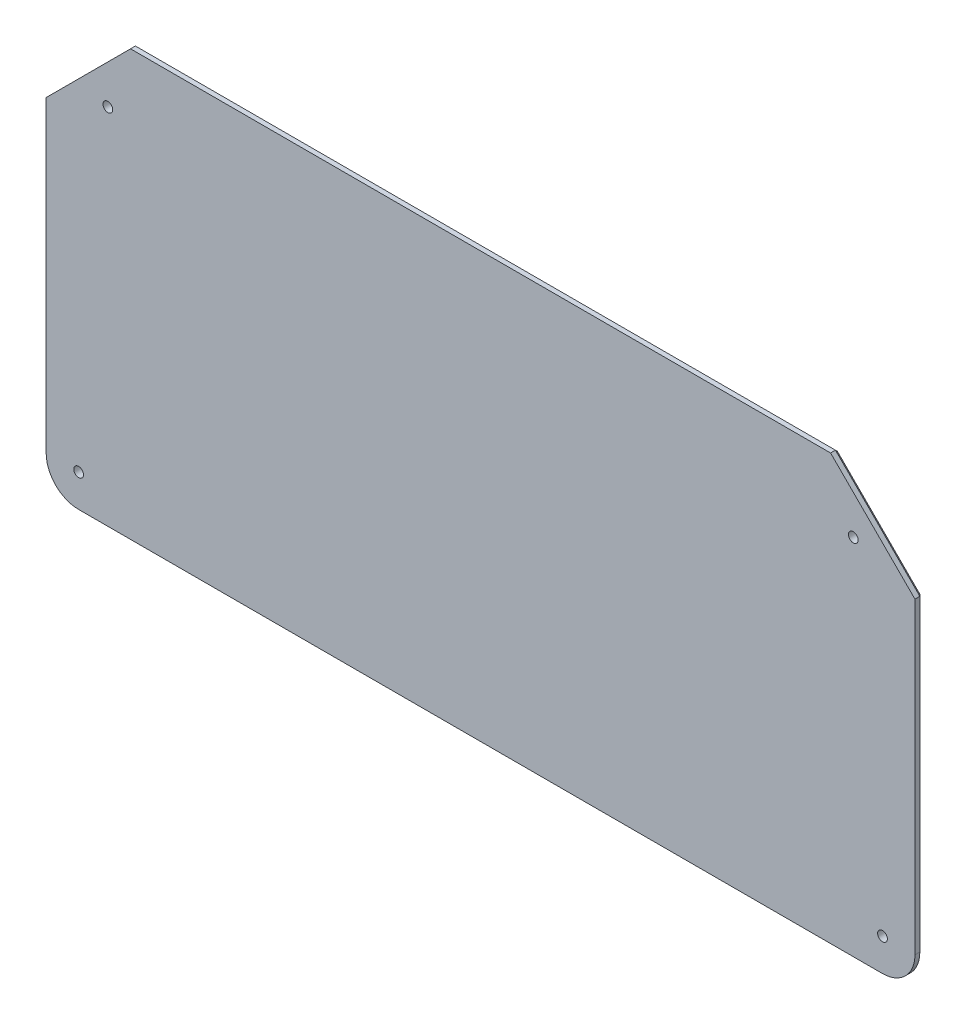
SolidWorks part; units mm, degrees
ref_plane "Front Plane" through (0, 0, 0) normal (0, 0, 1) x (1, 0, 0)
ref_plane "Top Plane" through (0, 0, 0) normal (0, 1, 0) x (1, 0, 0)
ref_plane "Right Plane" through (0, 0, 0) normal (1, 0, 0) x (0, 0, -1)
sketch "Sketch1" plane through (0, 0, 0) normal (0, 0, 1) x (1, 0, 0)
  line L0 (157.8919, 26.2701) -> (191.7747, 29.0915)
  line L1 (157.8919, 26.2701) -> (191.7747, 26.2701)
  line L2 (157.8919, 26.2701) -> (157.8919, 29.0915)
  line L3 (157.8919, 29.0915) -> (191.7747, 29.0915)
  line L4 (191.7747, 26.2701) -> (191.7747, 29.0915)
  line L5 (123.8919, 26.2701) -> (90.0092, 26.2701)
  line L6 (123.8919, 26.2701) -> (123.8919, 29.0915)
  line L7 (123.8919, 29.0915) -> (90.0092, 29.0915)
  line L8 (90.0092, 26.2701) -> (90.0092, 29.0915)
  line L9 (90.0092, 29.0915) -> (123.8919, 26.2701)
  line L10 (168.0919, 58.3601) -> (194.8735, 70.7292)
  line L11 (168.0919, 58.3601) -> (194.8735, 58.3601)
  line L12 (168.0919, 58.3601) -> (168.0919, 70.7292)
  line L13 (168.0919, 70.7292) -> (194.8735, 70.7292)
  line L14 (194.8735, 58.3601) -> (194.8735, 70.7292)
  line L15 (194.8735, 70.7292) -> (224.3587, 70.7292)
  line L16 (194.8735, 70.7292) -> (194.8735, 69.7923)
  line L17 (194.8735, 69.7923) -> (224.3587, 69.7923)
  line L18 (224.3587, 70.7292) -> (224.3587, 69.7923)
  line L19 (224.3587, 69.7923) -> (253.5106, 69.7923)
  line L20 (224.3587, 69.7923) -> (224.3587, 65.2742)
  line L21 (224.3587, 65.2742) -> (253.5106, 65.2742)
  line L22 (253.5106, 69.7923) -> (253.5106, 65.2742)
  line L23 (224.3587, 69.7923) -> (194.8735, 70.7292)
  line L24 (253.5106, 65.2742) -> (224.3587, 69.7923)
  line L25 (170.7502, 87.7401) -> (168.0919, 58.3601)
  line L26 (168.0919, 58.3601) -> (170.7502, 58.3601)
  line L27 (168.0919, 58.3601) -> (168.0919, 87.7401)
  line L28 (168.0919, 87.7401) -> (170.7502, 87.7401)
  line L29 (170.7502, 58.3601) -> (170.7502, 87.7401)
  line L30 (52.9966, 89.4705) -> (24.4119, 82.1791)
  line L31 (24.4119, 82.1791) -> (52.9966, 82.1791)
  line L32 (24.4119, 82.1791) -> (24.4119, 89.4705)
  line L33 (24.4119, 89.4705) -> (52.9966, 89.4705)
  line L34 (52.9966, 82.1791) -> (52.9966, 89.4705)
  line L35 (82.4966, 89.4705) -> (109.0019, 89.4705)
  line L36 (82.4966, 89.4705) -> (82.4966, 76.5201)
  line L37 (82.4966, 76.5201) -> (109.0019, 76.5201)
  line L38 (109.0019, 89.4705) -> (109.0019, 76.5201)
  line L39 (92.4554, 117.2387) -> (82.4966, 117.2387)
  line L40 (92.4554, 117.2387) -> (92.4554, 89.4705)
  line L41 (92.4554, 89.4705) -> (82.4966, 89.4705)
  line L42 (82.4966, 117.2387) -> (82.4966, 89.4705)
  line L43 (92.4554, 117.2387) -> (82.4966, 89.4705)
  line L44 (109.0019, 76.5201) -> (82.4966, 89.4705)
  circle A0 centre (123.8919, 26.2701) radius 14.25
  circle A1 centre (157.8919, 26.2701) radius 14.25
  circle A2 centre (90.0092, 29.0915) radius 14.25
  circle A3 centre (191.7747, 29.0915) radius 14.25
  circle A4 centre (82.4966, 89.4705) radius 11.25
  circle A5 centre (92.4554, 117.2387) radius 11.25
  circle A6 centre (52.9966, 89.4705) radius 11.25
  circle A7 centre (109.0019, 76.5201) radius 11.25
  circle A8 centre (24.4119, 82.1791) radius 11.25
  circle A9 centre (170.7502, 87.7401) radius 11.25
  circle A10 centre (168.0919, 58.3601) radius 11.25
  circle A11 centre (197.5318, 100.1092) radius 11.25
  circle A12 centre (194.8735, 70.7292) radius 11.25
  circle A13 centre (227.0169, 99.1723) radius 11.25
  circle A14 centre (224.3587, 69.7923) radius 11.25
  circle A15 centre (256.1689, 94.6541) radius 11.25
  circle A16 centre (253.5106, 65.2742) radius 11.25
  circle A17 centre (24.4119, 82.1791) radius 12
  circle A18 centre (52.9966, 89.4705) radius 12
  circle A19 centre (92.4554, 117.2387) radius 12
  circle A20 centre (82.4966, 89.4705) radius 12
  circle A21 centre (109.0019, 76.5201) radius 12
  circle A22 centre (168.0919, 58.3601) radius 12
  circle A23 centre (194.8735, 70.7292) radius 12
  circle A24 centre (224.3587, 69.7923) radius 12
  circle A25 centre (253.5106, 65.2742) radius 12
  circle A26 centre (256.1689, 94.6541) radius 12
  circle A27 centre (227.0169, 99.1723) radius 12
  circle A28 centre (197.5318, 100.1092) radius 12
  circle A29 centre (170.7502, 87.7401) radius 12
  circle A30 centre (191.7747, 29.0915) radius 15
  circle A31 centre (157.8919, 26.2701) radius 15
  circle A32 centre (123.8919, 26.2701) radius 15
  circle A33 centre (90.0092, 29.0915) radius 15
  circle A34 centre (173.429, 117.1182) radius 11.25
  circle A35 centre (173.429, 117.1182) radius 12
  dimension "D1" = 28.5
  dimension "D2" = 22.5
  dimension "D3" = 0.75
  dimension "D4" = 0.75
  dimension "D34" = 34
  dimension "D5" = 29.5
  dimension "D6" = 29.5
  dimension "D7" = 29.5
  dimension "D8" = 29.5
  dimension "D9" = 29.5
  dimension "D10" = 29.5
  dimension "D11" = 29.5
  dimension "D12" = 29.5
  dimension "D13" = 29.5
  dimension "D14" = 29.5
  dimension "D15" = 29.5
  dimension "D16" = 29.5
  dimension "D17" = 29.5
  dimension "D18" = 29.5
  dimension "D19" = 34
  dimension "D20" = 34
  dimension "D21" = 32.09
  dimension "D22" = 10.2
  dimension "D23" = 4.76
  dimension "D24" = 4.76
  dimension "D25" = 24.79
  dimension "D26" = 1.82
  dimension "D27" = 8.81
  dimension "D28" = 84.83
  dimension "D29" = 75.69
  dimension "D30" = 70.27
  dimension "D31" = 26.04
  dimension "D32" = 14.89
  dimension "D33" = 50.25
  dimension "D35" = 29.5
  dimension "D36" = 29.5
sketch "Sketch4" plane through (-30.2083, 20.075, 0) normal (0, 0, 1) x (0.9781, -0.2079, 0)
  line L0 (86.1706, 94.1917) -> (105.2206, 75.1417)
  line L1 (67.1206, 94.1917) -> (86.1706, 94.1917)
  line L2 (67.1206, 94.1917) -> (67.1206, 75.1417)
  line L3 (67.1206, 75.1417) -> (86.1706, 75.1417)
  line L4 (86.1706, 94.1917) -> (86.1706, 75.1417)
  line L5 (86.1706, 94.1917) -> (105.2206, 94.1917)
  line L6 (86.1706, 94.1917) -> (86.1706, 75.1417)
  line L7 (86.1706, 75.1417) -> (105.2206, 75.1417)
  line L8 (105.2206, 94.1917) -> (105.2206, 75.1417)
  line L9 (105.2206, 94.1917) -> (124.2706, 94.1917)
  line L10 (105.2206, 94.1917) -> (105.2206, 75.1417)
  line L11 (105.2206, 75.1417) -> (124.2706, 75.1417)
  line L12 (124.2706, 94.1917) -> (124.2706, 75.1417)
  line L13 (86.1706, 94.1917) -> (105.2206, 94.1917)
  line L14 (86.1706, 94.1917) -> (86.1706, 113.2417)
  line L15 (86.1706, 113.2417) -> (105.2206, 113.2417)
  line L16 (105.2206, 94.1917) -> (105.2206, 113.2417)
  line L17 (66.9585, 85.1784) -> (124.4326, 84.1551)
  point P14 (95.6956, 84.6667)
  point P15 (95.6956, 84.6667)
  dimension "D1" = 19.05
sketch "Sketch9" plane through (0, 0, 0) normal (0, 0, 1) x (1, 0, 0)
  line L1 (17.3619, 89.2291) -> (31.4619, 89.2291)
  line L2 (17.3619, 89.2291) -> (17.3619, 75.1291)
  line L3 (17.3619, 75.1291) -> (31.4619, 75.1291)
  line L4 (31.4619, 89.2291) -> (31.4619, 75.1291)
  line L5 (45.9466, 96.5205) -> (60.0466, 96.5205)
  line L6 (45.9466, 96.5205) -> (45.9466, 82.4205)
  line L7 (45.9466, 82.4205) -> (60.0466, 82.4205)
  line L8 (60.0466, 96.5205) -> (60.0466, 82.4205)
  line L9 (75.4466, 96.5205) -> (89.5466, 96.5205)
  line L10 (75.4466, 96.5205) -> (75.4466, 82.4205)
  line L11 (75.4466, 82.4205) -> (89.5466, 82.4205)
  line L12 (89.5466, 96.5205) -> (89.5466, 82.4205)
  line L13 (101.9519, 83.5701) -> (116.0519, 83.5701)
  line L14 (101.9519, 83.5701) -> (101.9519, 69.4701)
  line L15 (101.9519, 69.4701) -> (116.0519, 69.4701)
  line L16 (116.0519, 83.5701) -> (116.0519, 69.4701)
  line L17 (85.4054, 124.2887) -> (99.5054, 124.2887)
  line L18 (85.4054, 124.2887) -> (85.4054, 110.1887)
  line L19 (85.4054, 110.1887) -> (99.5054, 110.1887)
  line L20 (99.5054, 124.2887) -> (99.5054, 110.1887)
  line L21 (82.9592, 36.1415) -> (97.0592, 36.1415)
  line L22 (82.9592, 36.1415) -> (82.9592, 22.0415)
  line L23 (82.9592, 22.0415) -> (97.0592, 22.0415)
  line L24 (97.0592, 36.1415) -> (97.0592, 22.0415)
  line L25 (116.8419, 33.3201) -> (130.9419, 33.3201)
  line L26 (116.8419, 33.3201) -> (116.8419, 19.2201)
  line L27 (116.8419, 19.2201) -> (130.9419, 19.2201)
  line L28 (130.9419, 33.3201) -> (130.9419, 19.2201)
  line L29 (150.8419, 33.3201) -> (164.9419, 33.3201)
  line L30 (150.8419, 33.3201) -> (150.8419, 19.2201)
  line L31 (150.8419, 19.2201) -> (164.9419, 19.2201)
  line L32 (164.9419, 33.3201) -> (164.9419, 19.2201)
  line L33 (184.7247, 36.1415) -> (198.8247, 36.1415)
  line L34 (184.7247, 36.1415) -> (184.7247, 22.0415)
  line L35 (184.7247, 22.0415) -> (198.8247, 22.0415)
  line L36 (198.8247, 36.1415) -> (198.8247, 22.0415)
  line L37 (260.5606, 58.2242) -> (246.4606, 58.2242)
  line L38 (260.5606, 58.2242) -> (260.5606, 72.3242)
  line L39 (260.5606, 72.3242) -> (246.4606, 72.3242)
  line L40 (246.4606, 58.2242) -> (246.4606, 72.3242)
  line L41 (217.3087, 76.8423) -> (231.4087, 76.8423)
  line L42 (217.3087, 76.8423) -> (217.3087, 62.7423)
  line L43 (217.3087, 62.7423) -> (231.4087, 62.7423)
  line L44 (231.4087, 76.8423) -> (231.4087, 62.7423)
  line L45 (187.8235, 77.7792) -> (201.9235, 77.7792)
  line L46 (187.8235, 77.7792) -> (187.8235, 63.6792)
  line L47 (187.8235, 63.6792) -> (201.9235, 63.6792)
  line L48 (201.9235, 77.7792) -> (201.9235, 63.6792)
  line L49 (161.0419, 65.4101) -> (175.1419, 65.4101)
  line L50 (161.0419, 65.4101) -> (161.0419, 51.3101)
  line L51 (161.0419, 51.3101) -> (175.1419, 51.3101)
  line L52 (175.1419, 65.4101) -> (175.1419, 51.3101)
  line L53 (163.7002, 94.7901) -> (177.8002, 94.7901)
  line L54 (163.7002, 94.7901) -> (163.7002, 80.6901)
  line L55 (163.7002, 80.6901) -> (177.8002, 80.6901)
  line L56 (177.8002, 94.7901) -> (177.8002, 80.6901)
  line L57 (190.4818, 107.1592) -> (204.5818, 107.1592)
  line L58 (190.4818, 107.1592) -> (190.4818, 93.0592)
  line L59 (190.4818, 93.0592) -> (204.5818, 93.0592)
  line L60 (204.5818, 107.1592) -> (204.5818, 93.0592)
  line L61 (219.9669, 106.2223) -> (234.0669, 106.2223)
  line L62 (219.9669, 106.2223) -> (219.9669, 92.1223)
  line L63 (219.9669, 92.1223) -> (234.0669, 92.1223)
  line L64 (234.0669, 106.2223) -> (234.0669, 92.1223)
  line L65 (249.1189, 101.7041) -> (263.2189, 101.7041)
  line L66 (249.1189, 101.7041) -> (249.1189, 87.6041)
  line L67 (249.1189, 87.6041) -> (263.2189, 87.6041)
  line L68 (263.2189, 101.7041) -> (263.2189, 87.6041)
  line L69 (166.379, 124.1682) -> (180.479, 124.1682)
  line L70 (166.379, 124.1682) -> (166.379, 110.0682)
  line L71 (166.379, 110.0682) -> (180.479, 110.0682)
  line L72 (180.479, 124.1682) -> (180.479, 110.0682)
  point P72 (24.4119, 89.2291)
  point P74 (52.9966, 96.5205)
  point P76 (82.4966, 96.5205)
  point P78 (92.4554, 124.2887)
  point P80 (109.0019, 83.5701)
  point P82 (90.0092, 36.1415)
  point P84 (123.8919, 33.3201)
  point P86 (157.8919, 33.3201)
  point P88 (191.7747, 36.1415)
  point P90 (168.0919, 65.4101)
  point P92 (170.7502, 94.7901)
  point P94 (173.429, 124.1682)
  point P96 (197.5318, 107.1592)
  point P98 (227.0169, 106.2223)
  point P100 (256.1689, 101.7041)
  point P102 (194.8735, 77.7792)
  point P104 (224.3587, 76.8423)
  point P106 (253.5106, 72.3242)
  point P108 (17.3619, 82.1791)
  point P109 (45.9466, 89.4705)
  point P110 (75.4466, 89.4705)
  point P111 (101.9519, 76.5201)
  point P112 (85.4054, 117.2387)
  point P113 (82.9592, 29.0915)
  point P114 (116.8419, 26.2701)
  point P115 (150.8419, 26.2701)
  point P116 (184.7247, 29.0915)
  point P118 (161.0419, 58.3601)
  point P119 (187.8235, 70.7292)
  point P120 (217.3087, 69.7923)
  point P121 (246.4606, 65.2742)
  point P122 (163.7002, 87.7401)
  point P123 (190.4818, 100.1092)
  point P124 (219.9669, 99.1723)
  point P125 (249.1189, 94.6541)
  point P126 (166.379, 117.1182)
  dimension "D1" = 14.1
sketch "Sketch10" plane through (-22.0981, 19.3454, 0) normal (0, 0, 1) x (0.9781, -0.2079, 0)
  line L1 (61.5108, 90.7441) -> (75.6108, 90.7441)
  line L2 (61.5108, 90.7441) -> (61.5108, 76.6441)
  line L3 (61.5108, 76.6441) -> (75.6108, 76.6441)
  line L4 (75.6108, 90.7441) -> (75.6108, 76.6441)
  line L5 (80.5608, 90.7441) -> (94.6608, 90.7441)
  line L6 (80.5608, 90.7441) -> (80.5608, 76.6441)
  line L7 (80.5608, 76.6441) -> (94.6608, 76.6441)
  line L8 (94.6608, 90.7441) -> (94.6608, 76.6441)
  line L9 (99.6108, 90.7441) -> (113.7108, 90.7441)
  line L10 (99.6108, 90.7441) -> (99.6108, 76.6441)
  line L11 (99.6108, 76.6441) -> (113.7108, 76.6441)
  line L12 (113.7108, 90.7441) -> (113.7108, 76.6441)
  line L13 (80.5608, 109.7941) -> (94.6608, 109.7941)
  line L14 (80.5608, 109.7941) -> (80.5608, 95.6941)
  line L15 (80.5608, 95.6941) -> (94.6608, 95.6941)
  line L16 (94.6608, 109.7941) -> (94.6608, 95.6941)
  line L17 (50.5121, 89.6359) -> (53.4436, 75.8441) construction
  line L18 (59.0358, 93.2191) -> (78.0858, 93.2191) construction
  line L19 (78.0858, 112.2691) -> (97.1358, 112.2691) construction
  line L20 (97.1358, 93.2191) -> (116.1858, 93.2191) construction
  line L21 (78.0858, 93.2191) -> (78.0858, 112.2691) construction
  line L23 (59.0358, 93.2191) -> (59.0358, 74.1691) construction
  point P16 (75.6108, 83.6941)
  point P17 (94.6608, 83.6941)
  point P18 (113.7108, 83.6941)
  point P19 (87.6108, 90.7441)
  point P20 (87.6108, 109.7941)
  point P23 (68.5608, 90.7441)
  point P26 (68.5608, 93.2191)
  point P29 (87.6108, 112.2691)
  point P30 (106.6608, 90.7441)
  point P33 (106.6608, 93.2191)
  point P34 (80.5608, 102.7441)
  point P37 (78.0858, 102.7441)
  point P42 (59.0358, 83.6941)
  point P43 (61.5108, 83.6941)
sketch "Sketch14" plane through (0, 0, 0) normal (0, 0, 1) x (1, 0, 0)
  line L0 (165.1144, 80.6901) -> (163.7002, 82.1043)
  line L1 (163.7002, 93.3758) -> (165.1144, 94.7901)
  line L2 (177.8002, 93.3758) -> (176.386, 94.7901)
  line L3 (179.0648, 110.0682) -> (180.479, 111.4824)
  line L4 (166.379, 111.4824) -> (167.7932, 110.0682)
  line L5 (166.379, 122.754) -> (167.7932, 124.1682)
  line L6 (179.0648, 124.1682) -> (180.479, 122.754)
  line L7 (203.1676, 93.0592) -> (204.5818, 94.4734)
  line L8 (17.3619, 89.2291) -> (17.3619, 75.1291) construction
  line L9 (17.3619, 89.2291) -> (31.4619, 89.2291) construction
  line L10 (17.3619, 87.8149) -> (18.7761, 89.2291)
  line L11 (17.3619, 75.1291) -> (31.4619, 75.1291) construction
  line L12 (31.4619, 89.2291) -> (31.4619, 75.1291) construction
  line L13 (45.9466, 96.5205) -> (60.0466, 96.5205) construction
  line L14 (60.0466, 96.5205) -> (60.0466, 82.4205) construction
  line L15 (45.9466, 96.5205) -> (45.9466, 82.4205) construction
  line L16 (45.9466, 82.4205) -> (60.0466, 82.4205) construction
  line L17 (85.4054, 124.2887) -> (85.4054, 110.1887) construction
  line L18 (85.4054, 124.2887) -> (99.5054, 124.2887) construction
  line L19 (99.5054, 124.2887) -> (99.5054, 110.1887) construction
  line L20 (85.4054, 110.1887) -> (99.5054, 110.1887) construction
  line L21 (101.9519, 83.5701) -> (101.9519, 69.4701) construction
  line L22 (101.9519, 83.5701) -> (116.0519, 83.5701) construction
  line L23 (116.0519, 83.5701) -> (116.0519, 69.4701) construction
  line L24 (101.9519, 69.4701) -> (116.0519, 69.4701) construction
  line L25 (91.2712, 73.6044) -> (105.0631, 70.6729) construction
  line L26 (107.9947, 84.4647) -> (105.0631, 70.6729) construction
  line L27 (94.2028, 87.3963) -> (107.9947, 84.4647) construction
  line L28 (94.2028, 87.3963) -> (91.2712, 73.6044) construction
  line L29 (72.6375, 77.5651) -> (86.4294, 74.6336) construction
  line L30 (89.361, 88.4255) -> (86.4294, 74.6336) construction
  line L31 (75.5691, 91.357) -> (89.361, 88.4255) construction
  line L32 (75.5691, 91.357) -> (72.6375, 77.5651) construction
  line L33 (56.9354, 95.3177) -> (54.0038, 81.5259) construction
  line L34 (56.9354, 95.3177) -> (70.7273, 92.3862) construction
  line L35 (70.7273, 92.3862) -> (67.7957, 78.5943) construction
  line L36 (54.0038, 81.5259) -> (67.7957, 78.5943) construction
  line L37 (76.5983, 96.1988) -> (90.3901, 93.2673) construction
  line L38 (93.3217, 107.0592) -> (90.3901, 93.2673) construction
  line L39 (79.5298, 109.9907) -> (76.5983, 96.1988) construction
  line L40 (79.5298, 109.9907) -> (93.3217, 107.0592) construction
  line L41 (82.9592, 36.1415) -> (82.9592, 22.0415) construction
  line L42 (82.9592, 36.1415) -> (97.0592, 36.1415) construction
  line L43 (82.9592, 22.0415) -> (97.0592, 22.0415) construction
  line L44 (97.0592, 36.1415) -> (97.0592, 22.0415) construction
  line L45 (116.8419, 33.3201) -> (116.8419, 19.2201) construction
  line L46 (116.8419, 33.3201) -> (130.9419, 33.3201) construction
  line L47 (116.8419, 19.2201) -> (130.9419, 19.2201) construction
  line L48 (130.9419, 33.3201) -> (130.9419, 19.2201) construction
  line L49 (150.8419, 33.3201) -> (150.8419, 19.2201) construction
  line L50 (150.8419, 33.3201) -> (164.9419, 33.3201) construction
  line L51 (164.9419, 33.3201) -> (164.9419, 19.2201) construction
  line L52 (150.8419, 19.2201) -> (164.9419, 19.2201) construction
  line L53 (184.7247, 36.1415) -> (184.7247, 22.0415) construction
  line L54 (184.7247, 22.0415) -> (198.8247, 22.0415) construction
  line L55 (198.8247, 36.1415) -> (198.8247, 22.0415) construction
  line L56 (184.7247, 36.1415) -> (198.8247, 36.1415) construction
  line L57 (161.0419, 65.4101) -> (175.1419, 65.4101) construction
  line L58 (175.1419, 65.4101) -> (175.1419, 51.3101) construction
  line L59 (161.0419, 51.3101) -> (175.1419, 51.3101) construction
  line L60 (161.0419, 65.4101) -> (161.0419, 51.3101) construction
  line L61 (187.8235, 77.7792) -> (187.8235, 63.6792) construction
  line L62 (187.8235, 77.7792) -> (201.9235, 77.7792) construction
  line L63 (187.8235, 63.6792) -> (201.9235, 63.6792) construction
  line L64 (201.9235, 77.7792) -> (201.9235, 63.6792) construction
  line L65 (217.3087, 76.8423) -> (217.3087, 62.7423) construction
  line L66 (217.3087, 76.8423) -> (231.4087, 76.8423) construction
  line L67 (231.4087, 76.8423) -> (231.4087, 62.7423) construction
  line L68 (217.3087, 62.7423) -> (231.4087, 62.7423) construction
  line L69 (260.5606, 58.2242) -> (246.4606, 58.2242) construction
  line L70 (260.5606, 58.2242) -> (260.5606, 72.3242) construction
  line L71 (246.4606, 58.2242) -> (246.4606, 72.3242) construction
  line L72 (260.5606, 72.3242) -> (246.4606, 72.3242) construction
  line L73 (249.1189, 101.7041) -> (263.2189, 101.7041) construction
  line L74 (263.2189, 101.7041) -> (263.2189, 87.6041) construction
  line L75 (249.1189, 87.6041) -> (263.2189, 87.6041) construction
  line L76 (249.1189, 101.7041) -> (249.1189, 87.6041) construction
  line L77 (219.9669, 106.2223) -> (219.9669, 92.1223) construction
  line L78 (219.9669, 106.2223) -> (234.0669, 106.2223) construction
  line L79 (234.0669, 106.2223) -> (234.0669, 92.1223) construction
  line L80 (219.9669, 92.1223) -> (234.0669, 92.1223) construction
  line L81 (190.4818, 107.1592) -> (204.5818, 107.1592) construction
  line L82 (204.5818, 107.1592) -> (204.5818, 93.0592) construction
  line L83 (190.4818, 93.0592) -> (204.5818, 93.0592) construction
  line L84 (190.4818, 107.1592) -> (190.4818, 93.0592) construction
  line L85 (163.7002, 94.7901) -> (177.8002, 94.7901) construction
  line L86 (177.8002, 94.7901) -> (177.8002, 80.6901) construction
  line L87 (163.7002, 80.6901) -> (177.8002, 80.6901) construction
  line L88 (163.7002, 94.7901) -> (163.7002, 80.6901) construction
  line L89 (180.479, 124.1682) -> (180.479, 110.0682) construction
  line L90 (166.379, 110.0682) -> (180.479, 110.0682) construction
  line L91 (166.379, 124.1682) -> (166.379, 110.0682) construction
  line L92 (166.379, 124.1682) -> (180.479, 124.1682) construction
  line L93 (17.3619, 76.5433) -> (18.7761, 75.1291)
  line L94 (30.0477, 75.1291) -> (31.4619, 76.5433)
  line L95 (31.4619, 87.8149) -> (30.0477, 89.2291)
  line L96 (45.9466, 95.1063) -> (47.3608, 96.5205)
  line L97 (45.9466, 83.8347) -> (47.3608, 82.4205)
  line L98 (54.2979, 82.9092) -> (55.3871, 81.2318)
  line L99 (58.6323, 82.4205) -> (60.0466, 83.8347)
  line L100 (56.6413, 93.9344) -> (58.3187, 95.0237)
  line L101 (58.6323, 96.5205) -> (60.0466, 95.1063)
  line L102 (69.3439, 92.6802) -> (70.4332, 91.0029)
  line L103 (68.0897, 79.9776) -> (66.4124, 78.8883)
  line L104 (75.2751, 89.9737) -> (76.9524, 91.063)
  line L105 (72.9316, 78.9484) -> (74.0208, 77.2711)
  line L106 (85.0461, 74.9276) -> (86.7234, 76.0169)
  line L107 (89.0669, 87.0421) -> (87.9777, 88.7195)
  line L108 (89.0068, 93.5613) -> (90.6842, 94.6506)
  line L109 (76.8923, 97.5822) -> (77.9816, 95.9048)
  line L110 (91.9384, 107.3532) -> (93.0277, 105.6759)
  line L111 (79.2358, 108.6074) -> (80.9131, 109.6967)
  line L112 (85.4054, 111.6029) -> (86.8196, 110.1887)
  line L113 (98.0912, 110.1887) -> (99.5054, 111.6029)
  line L114 (98.0912, 124.2887) -> (99.5054, 122.8745)
  line L115 (85.4054, 122.8745) -> (86.8196, 124.2887)
  line L116 (93.9088, 86.013) -> (95.5861, 87.1023)
  line L117 (91.5653, 74.9877) -> (92.6546, 73.3104)
  line L118 (103.6798, 70.9669) -> (105.3572, 72.0562)
  line L119 (106.6114, 84.7588) -> (107.7006, 83.0814)
  line L120 (101.9519, 82.1559) -> (103.3662, 83.5701)
  line L121 (101.9519, 70.8843) -> (103.3662, 69.4701)
  line L122 (114.6377, 69.4701) -> (116.0519, 70.8843)
  line L123 (116.0519, 82.1559) -> (114.6377, 83.5701)
  line L124 (82.9592, 34.7272) -> (84.3734, 36.1415)
  line L125 (82.9592, 23.4557) -> (84.3734, 22.0415)
  line L126 (95.645, 22.0415) -> (97.0592, 23.4557)
  line L127 (97.0592, 34.7272) -> (95.645, 36.1415)
  line L128 (116.8419, 31.9059) -> (118.2562, 33.3201)
  line L129 (116.8419, 20.6343) -> (118.2562, 19.2201)
  line L130 (129.5277, 19.2201) -> (130.9419, 20.6343)
  line L131 (130.9419, 31.9059) -> (129.5277, 33.3201)
  line L132 (150.8419, 31.9059) -> (152.2562, 33.3201)
  line L133 (150.8419, 20.6343) -> (152.2562, 19.2201)
  line L134 (163.5277, 19.2201) -> (164.9419, 20.6343)
  line L135 (164.9419, 31.9059) -> (163.5277, 33.3201)
  line L136 (184.7247, 34.7272) -> (186.1389, 36.1415)
  line L137 (184.7247, 23.4557) -> (186.1389, 22.0415)
  line L138 (197.4105, 22.0415) -> (198.8247, 23.4557)
  line L139 (198.8247, 34.7272) -> (197.4105, 36.1415)
  line L140 (173.7277, 51.3101) -> (175.1419, 52.7243)
  line L141 (161.0419, 52.7243) -> (162.4562, 51.3101)
  line L142 (161.0419, 63.9959) -> (162.4562, 65.4101)
  line L143 (173.7277, 65.4101) -> (175.1419, 63.9959)
  line L144 (187.8235, 65.0934) -> (189.2378, 63.6792)
  line L145 (200.5093, 63.6792) -> (201.9235, 65.0934)
  line L146 (200.5093, 77.7792) -> (201.9235, 76.365)
  line L147 (187.8235, 76.365) -> (189.2378, 77.7792)
  line L148 (176.386, 80.6901) -> (177.8002, 82.1043)
  line L149 (204.5818, 105.745) -> (203.1676, 107.1592)
  line L150 (191.896, 107.1592) -> (190.4818, 105.745)
  line L151 (190.4818, 94.4734) -> (191.896, 93.0592)
  line L152 (219.9669, 104.8081) -> (221.3812, 106.2223)
  line L153 (232.6527, 106.2223) -> (234.0669, 104.8081)
  line L154 (234.0669, 93.5365) -> (232.6527, 92.1223)
  line L155 (219.9669, 93.5365) -> (221.3812, 92.1223)
  line L156 (229.9944, 76.8423) -> (231.4087, 75.4281)
  line L157 (217.3087, 75.4281) -> (218.7229, 76.8423)
  line L158 (217.3087, 64.1565) -> (218.7229, 62.7423)
  line L159 (229.9944, 62.7423) -> (231.4087, 64.1565)
  line L160 (259.1464, 72.3242) -> (260.5606, 70.9099)
  line L161 (246.4606, 70.9099) -> (247.8748, 72.3242)
  line L162 (259.1464, 58.2242) -> (260.5606, 59.6384)
  line L163 (247.8748, 58.2242) -> (246.4606, 59.6384)
  line L164 (261.8047, 87.6041) -> (263.2189, 89.0183)
  line L165 (249.1189, 89.0183) -> (250.5331, 87.6041)
  line L166 (249.1189, 100.2899) -> (250.5331, 101.7041)
  line L167 (261.8047, 101.7041) -> (263.2189, 100.2899)
  line L168 (75.4466, 96.5205) -> (75.4466, 82.4205) construction
  line L169 (75.4466, 96.5205) -> (89.5466, 96.5205) construction
  line L170 (89.5466, 96.5205) -> (89.5466, 82.4205) construction
  line L171 (75.4466, 82.4205) -> (89.5466, 82.4205) construction
  line L172 (76.8608, 96.5205) -> (75.4466, 95.1063)
  line L173 (88.1323, 96.5205) -> (89.5466, 95.1063)
  line L174 (89.5466, 83.8347) -> (88.1323, 82.4205)
  line L175 (75.4466, 83.8347) -> (76.8608, 82.4205)
  arc A0 (17.3619, 87.8149) -> (18.7761, 89.2291) centre (18.069, 88.522) cw
  arc A1 (18.7761, 75.1291) -> (17.3619, 76.5433) centre (18.069, 75.8362) cw
  arc A2 (31.4619, 76.5433) -> (30.0477, 75.1291) centre (30.7548, 75.8362) cw
  arc A3 (30.0477, 89.2291) -> (31.4619, 87.8149) centre (30.7548, 88.522) cw
  arc A4 (58.6323, 96.5205) -> (60.0466, 95.1063) centre (59.3394, 95.8134) cw
  arc A5 (45.9466, 95.1063) -> (47.3608, 96.5205) centre (46.6537, 95.8134) cw
  arc A6 (47.3608, 82.4205) -> (45.9466, 83.8347) centre (46.6537, 83.1276) cw
  arc A7 (60.0466, 83.8347) -> (58.6323, 82.4205) centre (59.3394, 83.1276) cw
  arc A8 (85.4054, 122.8745) -> (86.8196, 124.2887) centre (86.1125, 123.5816) cw
  arc A9 (98.0912, 124.2887) -> (99.5054, 122.8745) centre (98.7983, 123.5816) cw
  arc A10 (99.5054, 111.6029) -> (98.0912, 110.1887) centre (98.7983, 110.8958) cw
  arc A11 (85.4054, 111.6029) -> (86.8196, 110.1887) centre (86.1125, 110.8958) ccw
  arc A12 (101.9519, 82.1559) -> (103.3662, 83.5701) centre (102.6591, 82.863) cw
  arc A13 (114.6377, 83.5701) -> (116.0519, 82.1559) centre (115.3448, 82.863) cw
  arc A14 (116.0519, 70.8843) -> (114.6377, 69.4701) centre (115.3448, 70.1772) cw
  arc A15 (101.9519, 70.8843) -> (103.3662, 69.4701) centre (102.6591, 70.1772) ccw
  arc A16 (103.6798, 70.9669) -> (105.3572, 72.0562) centre (104.5185, 71.5115) ccw
  arc A17 (106.6114, 84.7588) -> (107.7006, 83.0814) centre (107.156, 83.9201) cw
  arc A18 (93.9088, 86.013) -> (95.5861, 87.1023) centre (94.7474, 86.5576) cw
  arc A19 (91.5653, 74.9877) -> (92.6546, 73.3104) centre (92.1099, 74.1491) ccw
  arc A20 (85.0461, 74.9276) -> (86.7234, 76.0169) centre (85.8848, 75.4722) ccw
  arc A21 (87.9777, 88.7195) -> (89.0669, 87.0421) centre (88.5223, 87.8808) cw
  arc A22 (75.2751, 89.9737) -> (76.9524, 91.063) centre (76.1137, 90.5183) cw
  arc A23 (72.9316, 78.9484) -> (74.0208, 77.2711) centre (73.4762, 78.1098) ccw
  arc A24 (56.6413, 93.9344) -> (58.3187, 95.0237) centre (57.48, 94.4791) cw
  arc A25 (69.3439, 92.6802) -> (70.4332, 91.0029) centre (69.8886, 91.8415) cw
  arc A26 (68.0897, 79.9776) -> (66.4124, 78.8883) centre (67.2511, 79.433) cw
  arc A27 (54.2979, 82.9092) -> (55.3871, 81.2318) centre (54.8425, 82.0705) ccw
  arc A28 (89.0068, 93.5613) -> (90.6842, 94.6506) centre (89.8455, 94.106) ccw
  arc A29 (76.8923, 97.5822) -> (77.9816, 95.9048) centre (77.4369, 96.7435) ccw
  arc A30 (79.2358, 108.6074) -> (80.9131, 109.6967) centre (80.0744, 109.1521) cw
  arc A31 (91.9384, 107.3532) -> (93.0277, 105.6759) centre (92.483, 106.5145) cw
  arc A32 (82.9592, 34.7272) -> (84.3734, 36.1415) centre (83.6663, 35.4344) cw
  arc A33 (82.9592, 23.4557) -> (84.3734, 22.0415) centre (83.6663, 22.7486) ccw
  arc A34 (95.645, 22.0415) -> (97.0592, 23.4557) centre (96.3521, 22.7486) ccw
  arc A35 (95.645, 36.1415) -> (97.0592, 34.7272) centre (96.3521, 35.4344) cw
  arc A36 (116.8419, 31.9059) -> (118.2562, 33.3201) centre (117.5491, 32.613) cw
  arc A37 (116.8419, 20.6343) -> (118.2562, 19.2201) centre (117.5491, 19.9272) ccw
  arc A38 (129.5277, 19.2201) -> (130.9419, 20.6343) centre (130.2348, 19.9272) ccw
  arc A39 (129.5277, 33.3201) -> (130.9419, 31.9059) centre (130.2348, 32.613) cw
  arc A40 (150.8419, 31.9059) -> (152.2562, 33.3201) centre (151.5491, 32.613) cw
  arc A41 (163.5277, 33.3201) -> (164.9419, 31.9059) centre (164.2348, 32.613) cw
  arc A42 (164.9419, 20.6343) -> (163.5277, 19.2201) centre (164.2348, 19.9272) cw
  arc A43 (150.8419, 20.6343) -> (152.2562, 19.2201) centre (151.5491, 19.9272) ccw
  arc A44 (184.7247, 23.4557) -> (186.1389, 22.0415) centre (185.4318, 22.7486) ccw
  arc A45 (197.4105, 22.0415) -> (198.8247, 23.4557) centre (198.1176, 22.7486) ccw
  arc A46 (197.4105, 36.1415) -> (198.8247, 34.7272) centre (198.1176, 35.4344) cw
  arc A47 (184.7247, 34.7272) -> (186.1389, 36.1415) centre (185.4318, 35.4344) cw
  arc A48 (173.7277, 65.4101) -> (175.1419, 63.9959) centre (174.4348, 64.703) cw
  arc A49 (175.1419, 52.7243) -> (173.7277, 51.3101) centre (174.4348, 52.0172) cw
  arc A50 (161.0419, 52.7243) -> (162.4562, 51.3101) centre (161.7491, 52.0172) ccw
  arc A51 (161.0419, 63.9959) -> (162.4562, 65.4101) centre (161.7491, 64.703) cw
  arc A52 (187.8235, 76.365) -> (189.2378, 77.7792) centre (188.5306, 77.0721) cw
  arc A53 (187.8235, 65.0934) -> (189.2378, 63.6792) centre (188.5306, 64.3863) ccw
  arc A54 (200.5093, 63.6792) -> (201.9235, 65.0934) centre (201.2164, 64.3863) ccw
  arc A55 (200.5093, 77.7792) -> (201.9235, 76.365) centre (201.2164, 77.0721) cw
  arc A56 (217.3087, 75.4281) -> (218.7229, 76.8423) centre (218.0158, 76.1352) cw
  arc A57 (229.9944, 76.8423) -> (231.4087, 75.4281) centre (230.7016, 76.1352) cw
  arc A58 (231.4087, 64.1565) -> (229.9944, 62.7423) centre (230.7016, 63.4494) cw
  arc A59 (217.3087, 64.1565) -> (218.7229, 62.7423) centre (218.0158, 63.4494) ccw
  arc A60 (259.1464, 58.2242) -> (260.5606, 59.6384) centre (259.8535, 58.9313) ccw
  arc A61 (246.4606, 59.6384) -> (247.8748, 58.2242) centre (247.1677, 58.9313) ccw
  arc A62 (246.4606, 70.9099) -> (247.8748, 72.3242) centre (247.1677, 71.617) cw
  arc A63 (259.1464, 72.3242) -> (260.5606, 70.9099) centre (259.8535, 71.617) cw
  arc A64 (261.8047, 101.7041) -> (263.2189, 100.2899) centre (262.5118, 100.997) cw
  arc A65 (263.2189, 89.0183) -> (261.8047, 87.6041) centre (262.5118, 88.3112) cw
  arc A66 (250.5331, 87.6041) -> (249.1189, 89.0183) centre (249.826, 88.3112) cw
  arc A67 (249.1189, 100.2899) -> (250.5331, 101.7041) centre (249.826, 100.997) cw
  arc A68 (219.9669, 104.8081) -> (221.3812, 106.2223) centre (220.674, 105.5152) cw
  arc A69 (232.6527, 106.2223) -> (234.0669, 104.8081) centre (233.3598, 105.5152) cw
  arc A70 (234.0669, 93.5365) -> (232.6527, 92.1223) centre (233.3598, 92.8294) cw
  arc A71 (221.3812, 92.1223) -> (219.9669, 93.5365) centre (220.674, 92.8294) cw
  arc A72 (203.1676, 107.1592) -> (204.5818, 105.745) centre (203.8747, 106.4521) cw
  arc A73 (204.5818, 94.4734) -> (203.1676, 93.0592) centre (203.8747, 93.7663) cw
  arc A74 (191.896, 93.0592) -> (190.4818, 94.4734) centre (191.1889, 93.7663) cw
  arc A75 (190.4818, 105.745) -> (191.896, 107.1592) centre (191.1889, 106.4521) cw
  arc A76 (176.386, 94.7901) -> (177.8002, 93.3758) centre (177.0931, 94.0829) cw
  arc A77 (177.8002, 82.1043) -> (176.386, 80.6901) centre (177.0931, 81.3972) cw
  arc A78 (165.1144, 80.6901) -> (163.7002, 82.1043) centre (164.4073, 81.3972) cw
  arc A79 (163.7002, 93.3758) -> (165.1144, 94.7901) centre (164.4073, 94.0829) cw
  arc A80 (180.479, 111.4824) -> (179.0648, 110.0682) centre (179.7719, 110.7753) cw
  arc A81 (167.7932, 110.0682) -> (166.379, 111.4824) centre (167.0861, 110.7753) cw
  arc A82 (179.0648, 124.1682) -> (180.479, 122.754) centre (179.7719, 123.4611) cw
  arc A83 (166.379, 122.754) -> (167.7932, 124.1682) centre (167.0861, 123.4611) cw
  arc A84 (75.4466, 95.1063) -> (76.8608, 96.5205) centre (76.1537, 95.8134) cw
  arc A85 (88.1323, 96.5205) -> (89.5466, 95.1063) centre (88.8394, 95.8134) cw
  arc A86 (89.5466, 83.8347) -> (88.1323, 82.4205) centre (88.8394, 83.1276) cw
  arc A87 (76.8608, 82.4205) -> (75.4466, 83.8347) centre (76.1537, 83.1276) cw
  dimension "D1" = 45
  dimension "D2" = 1
  dimension "D71" = 45
  dimension "D3" = 45
  dimension "D4" = 45
  dimension "D5" = 45
  dimension "D6" = 45
  dimension "D7" = 45
  dimension "D8" = 45
  dimension "D9" = 45
  dimension "D10" = 45
  dimension "D11" = 45
  dimension "D12" = 45
  dimension "D13" = 45
  dimension "D14" = 45
  dimension "D15" = 45
  dimension "D16" = 45
  dimension "D17" = 45
  dimension "D18" = 45
  dimension "D19" = 45
  dimension "D20" = 45
  dimension "D21" = 45
  dimension "D22" = 45
  dimension "D23" = 45
  dimension "D24" = 45
  dimension "D25" = 45
  dimension "D26" = 45
  dimension "D27" = 45
  dimension "D28" = 45
  dimension "D29" = 45
  dimension "D30" = 45
  dimension "D31" = 45
  dimension "D32" = 45
  dimension "D33" = 45
  dimension "D34" = 45
  dimension "D35" = 45
  dimension "D36" = 45
  dimension "D37" = 45
  dimension "D38" = 45
  dimension "D39" = 45
  dimension "D40" = 45
  dimension "D41" = 45
  dimension "D42" = 45
  dimension "D43" = 45
  dimension "D44" = 45
  dimension "D45" = 45
  dimension "D46" = 45
  dimension "D47" = 45
  dimension "D48" = 45
  dimension "D49" = 45
  dimension "D50" = 45
  dimension "D51" = 45
  dimension "D52" = 45
  dimension "D53" = 45
  dimension "D54" = 45
  dimension "D55" = 45
  dimension "D56" = 45
  dimension "D57" = 45
  dimension "D58" = 45
  dimension "D59" = 45
  dimension "D60" = 45
  dimension "D61" = 45
  dimension "D62" = 45
  dimension "D63" = 45
  dimension "D64" = 45
  dimension "D65" = 45
  dimension "D66" = 45
  dimension "D67" = 45
  dimension "D68" = 45
  dimension "D69" = 45
  dimension "D70" = 45
  dimension "D72" = 45
  dimension "D73" = 45
  dimension "D74" = 45
  dimension "D75" = 45
  dimension "D76" = 45
  dimension "D77" = 45
  dimension "D78" = 45
  dimension "D79" = 45
  dimension "D80" = 45
  dimension "D81" = 45
  dimension "D82" = 45
  dimension "D83" = 45
  dimension "D84" = 45
  dimension "D85" = 45
  dimension "D86" = 45
  dimension "D87" = 45
  dimension "D88" = 45
  dimension "D89" = 45
sketch "Sketch16" plane through (0, 0, 0) normal (0, 0, 1) x (1, 0, 0)
  line L0 (81.0092, 30.6915) -> (99.0092, 30.6915)
  line L5 (17.3619, 89.2291) -> (17.3619, 75.1291) construction
  line L6 (81.0092, 30.6915) -> (81.0092, 27.4915)
  line L7 (17.3619, 75.1291) -> (31.4619, 75.1291) construction
  line L8 (15.4119, 83.7791) -> (33.4119, 83.7791)
  line L9 (15.4119, 83.7791) -> (15.4119, 80.5791)
  line L10 (15.4119, 80.5791) -> (33.4119, 80.5791)
  line L11 (33.4119, 83.7791) -> (33.4119, 80.5791)
  line L12 (81.0092, 27.4915) -> (99.0092, 27.4915)
  line L13 (99.0092, 30.6915) -> (99.0092, 27.4915)
  line L14 (114.8919, 27.8701) -> (132.8919, 27.8701)
  line L15 (114.8919, 27.8701) -> (114.8919, 24.6701)
  line L16 (114.8919, 24.6701) -> (132.8919, 24.6701)
  line L17 (132.8919, 27.8701) -> (132.8919, 24.6701)
  line L18 (148.8919, 27.8701) -> (166.8919, 27.8701)
  line L19 (148.8919, 27.8701) -> (148.8919, 24.6701)
  line L20 (148.8919, 24.6701) -> (166.8919, 24.6701)
  line L21 (166.8919, 27.8701) -> (166.8919, 24.6701)
  line L22 (182.7747, 30.6915) -> (200.7747, 30.6915)
  line L23 (182.7747, 30.6915) -> (182.7747, 27.4915)
  line L24 (182.7747, 27.4915) -> (200.7747, 27.4915)
  line L25 (200.7747, 30.6915) -> (200.7747, 27.4915)
  line L26 (43.9966, 91.0705) -> (61.9966, 91.0705)
  line L27 (43.9966, 91.0705) -> (43.9966, 87.8705)
  line L28 (43.9966, 87.8705) -> (61.9966, 87.8705)
  line L29 (61.9966, 91.0705) -> (61.9966, 87.8705)
  line L30 (73.4966, 91.0705) -> (91.4966, 91.0705)
  line L31 (73.4966, 91.0705) -> (73.4966, 87.8705)
  line L32 (73.4966, 87.8705) -> (91.4966, 87.8705)
  line L33 (91.4966, 91.0705) -> (91.4966, 87.8705)
  line L34 (100.0019, 78.1201) -> (118.0019, 78.1201)
  line L35 (100.0019, 78.1201) -> (100.0019, 74.9201)
  line L36 (100.0019, 74.9201) -> (118.0019, 74.9201)
  line L37 (118.0019, 78.1201) -> (118.0019, 74.9201)
  line L38 (83.4554, 118.8387) -> (101.4554, 118.8387)
  line L39 (83.4554, 118.8387) -> (83.4554, 115.6387)
  line L40 (83.4554, 115.6387) -> (101.4554, 115.6387)
  line L41 (101.4554, 118.8387) -> (101.4554, 115.6387)
  line L42 (164.429, 118.7182) -> (182.429, 118.7182)
  line L43 (164.429, 118.7182) -> (164.429, 115.5182)
  line L44 (164.429, 115.5182) -> (182.429, 115.5182)
  line L45 (182.429, 118.7182) -> (182.429, 115.5182)
  line L46 (161.7502, 89.3401) -> (179.7502, 89.3401)
  line L47 (161.7502, 89.3401) -> (161.7502, 86.1401)
  line L48 (161.7502, 86.1401) -> (179.7502, 86.1401)
  line L49 (179.7502, 89.3401) -> (179.7502, 86.1401)
  line L50 (188.5318, 101.7092) -> (206.5318, 101.7092)
  line L51 (188.5318, 101.7092) -> (188.5318, 98.5092)
  line L52 (188.5318, 98.5092) -> (206.5318, 98.5092)
  line L53 (206.5318, 101.7092) -> (206.5318, 98.5092)
  line L54 (159.0919, 59.9601) -> (177.0919, 59.9601)
  line L55 (159.0919, 59.9601) -> (159.0919, 56.7601)
  line L56 (159.0919, 56.7601) -> (177.0919, 56.7601)
  line L57 (177.0919, 59.9601) -> (177.0919, 56.7601)
  line L58 (185.8735, 72.3292) -> (203.8735, 72.3292)
  line L59 (185.8735, 72.3292) -> (185.8735, 69.1292)
  line L60 (185.8735, 69.1292) -> (203.8735, 69.1292)
  line L61 (203.8735, 72.3292) -> (203.8735, 69.1292)
  line L62 (218.0169, 100.7723) -> (236.0169, 100.7723)
  line L63 (218.0169, 100.7723) -> (218.0169, 97.5723)
  line L64 (218.0169, 97.5723) -> (236.0169, 97.5723)
  line L65 (236.0169, 100.7723) -> (236.0169, 97.5723)
  line L66 (215.3587, 71.3923) -> (233.3587, 71.3923)
  line L67 (215.3587, 71.3923) -> (215.3587, 68.1923)
  line L68 (215.3587, 68.1923) -> (233.3587, 68.1923)
  line L69 (233.3587, 71.3923) -> (233.3587, 68.1923)
  line L70 (247.1689, 96.2541) -> (265.1689, 96.2541)
  line L71 (247.1689, 96.2541) -> (247.1689, 93.0541)
  line L72 (247.1689, 93.0541) -> (265.1689, 93.0541)
  line L73 (265.1689, 96.2541) -> (265.1689, 93.0541)
  line L74 (244.5106, 66.8742) -> (262.5106, 66.8742)
  line L75 (244.5106, 66.8742) -> (244.5106, 63.6742)
  line L76 (244.5106, 63.6742) -> (262.5106, 63.6742)
  line L77 (262.5106, 66.8742) -> (262.5106, 63.6742)
  circle A0 centre (15.4119, 82.1791) radius 1.6
  circle A1 centre (33.4119, 82.1791) radius 1.6
  circle A2 centre (81.0092, 29.0915) radius 1.6
  circle A3 centre (99.0092, 29.0915) radius 1.6
  circle A4 centre (114.8919, 26.2701) radius 1.6
  circle A5 centre (132.8919, 26.2701) radius 1.6
  circle A6 centre (148.8919, 26.2701) radius 1.6
  circle A7 centre (166.8919, 26.2701) radius 1.6
  circle A8 centre (182.7747, 29.0915) radius 1.6
  circle A9 centre (200.7747, 29.0915) radius 1.6
  circle A10 centre (43.9966, 89.4705) radius 1.6
  circle A11 centre (61.9966, 89.4705) radius 1.6
  circle A12 centre (73.4966, 89.4705) radius 1.6
  circle A13 centre (91.4966, 89.4705) radius 1.6
  circle A14 centre (100.0019, 76.5201) radius 1.6
  circle A15 centre (118.0019, 76.5201) radius 1.6
  circle A16 centre (83.4554, 117.2387) radius 1.6
  circle A17 centre (101.4554, 117.2387) radius 1.6
  circle A18 centre (164.429, 117.1182) radius 1.6
  circle A19 centre (182.429, 117.1182) radius 1.6
  circle A20 centre (161.7502, 87.7401) radius 1.6
  circle A21 centre (179.7502, 87.7401) radius 1.6
  circle A22 centre (188.5318, 100.1092) radius 1.6
  circle A23 centre (206.5318, 100.1092) radius 1.6
  circle A24 centre (159.0919, 58.3601) radius 1.6
  circle A25 centre (177.0919, 58.3601) radius 1.6
  circle A26 centre (185.8735, 70.7292) radius 1.6
  circle A27 centre (203.8735, 70.7292) radius 1.6
  circle A28 centre (218.0169, 99.1723) radius 1.6
  circle A29 centre (236.0169, 99.1723) radius 1.6
  circle A30 centre (215.3587, 69.7923) radius 1.6
  circle A31 centre (233.3587, 69.7923) radius 1.6
  circle A32 centre (247.1689, 94.6541) radius 1.6
  circle A33 centre (265.1689, 94.6541) radius 1.6
  circle A34 centre (244.5106, 65.2742) radius 1.6
  circle A35 centre (262.5106, 65.2742) radius 1.6
  point P2 (24.4119, 75.1291)
  point P6 (17.3619, 82.1791)
  point P14 (24.4119, 80.5791)
  point P53 (90.0092, 30.6915)
  point P57 (123.8919, 27.8701)
  point P60 (157.8919, 27.8701)
  point P63 (191.7747, 30.6915)
  point P73 (52.9966, 91.0705)
  point P83 (82.4966, 91.0705)
  point P93 (109.0019, 78.1201)
  point P103 (92.4554, 118.8387)
  point P113 (173.429, 118.7182)
  point P123 (170.7502, 89.3401)
  point P133 (197.5318, 101.7092)
  point P143 (168.0919, 59.9601)
  point P153 (194.8735, 72.3292)
  point P163 (227.0169, 100.7723)
  point P173 (224.3587, 71.3923)
  point P183 (256.1689, 96.2541)
  point P193 (253.5106, 66.8742)
  dimension "D1" = 3.2
  dimension "D2" = 18
sketch "Sketch8" plane through (0, 0, 0) normal (0, 0, 1) x (1, 0, 0)
  line L0 (52.2844, 74.6389) -> (82.4966, 89.4705)
  line L1 (86.9403, 110.9459) -> (79.0189, 73.6784)
  line L2 (77.6235, 112.9262) -> (96.2572, 108.9655) construction
  line L3 (69.702, 75.6588) -> (88.3357, 71.6981) construction
  line L4 (53.3861, 72.3947) -> (55.5425, 73.4534)
  line L5 (99.6829, 63.2465) -> (101.1557, 61.3487)
  line L6 (103.1308, 62.8814) -> (82.4966, 89.4705)
  line L13 (93.9017, 130.158) -> (94.0202, 130.4883)
  line L14 (99.5495, 128.1325) -> (99.6679, 128.4628)
  line L16 (99.4417, 62.7418) -> (100.7607, 61.0421)
  line L17 (55.5377, 72.894) -> (53.6064, 71.9459)
  line L19 (82.4966, 89.4705) -> (96.8441, 129.4755)
  circle A1 centre (57.4203, 106.4022) radius 2.5
  circle A2 centre (106.0456, 106.2134) radius 2.5
  circle A3 centre (76.7673, 63.0854) radius 2.5
  circle A4 centre (52.9966, 89.4705) radius 13
  circle A6 centre (92.4554, 117.2387) radius 13
  circle A7 centre (109.0019, 76.5201) radius 13
  circle A8 centre (82.4966, 89.4705) radius 25
  arc A10 (50.3337, 102.1949) -> (81.377, 124.0408) centre (40.5107, 149.1329) ccw
  circle A11 centre (103.1308, 62.8814) radius 2.5
  circle A12 centre (52.2844, 74.6389) radius 2.5
  circle A13 centre (96.8441, 129.4755) radius 2.5
  circle A14 centre (52.2844, 74.6389) radius 3
  circle A15 centre (103.1308, 62.8814) radius 3
  circle A16 centre (96.8441, 129.4755) radius 3
  arc A17 (104.9258, 113.5659) -> (115.3756, 87.8504) centre (126.3001, 107.2707) ccw
  arc A18 (45.7038, 78.7088) -> (110.8301, 63.6492) centre (97.7768, 155.5511) ccw
  circle A19 centre (92.4554, 117.2387) radius 15
  circle A20 centre (109.0019, 76.5201) radius 15
  circle A21 centre (52.9966, 89.4705) radius 15
  circle A22 centre (82.4966, 89.4705) radius 27
  arc A23 (44.5818, 77.0531) -> (111.1113, 61.6691) centre (97.7768, 155.5511) ccw
  arc A24 (49.924, 104.1525) -> (79.6727, 125.0873) centre (40.5107, 149.1329) ccw
  arc A25 (106.8443, 113.0008) -> (116.3562, 89.5935) centre (126.3001, 107.2707) ccw
  circle A26 centre (52.9966, 89.4705) radius 12.5
  circle A27 centre (109.0019, 76.5201) radius 12.5
  circle A28 centre (92.4554, 117.2387) radius 12.5
  circle A29 centre (82.4966, 89.4705) radius 24.5
  arc A30 (104.4462, 113.7071) -> (115.1305, 87.4146) centre (126.3001, 107.2707) ccw
  arc A31 (110.7597, 64.1443) -> (45.9842, 79.1227) centre (97.7768, 155.5511) cw
  arc A32 (50.4361, 101.7055) -> (81.8031, 123.7792) centre (40.5107, 149.1329) ccw
  circle A33 centre (52.9966, 89.4705) radius 15.5
  circle A34 centre (109.0019, 76.5201) radius 15.5
  circle A35 centre (92.4554, 117.2387) radius 15.5
  circle A36 centre (82.4966, 89.4705) radius 27.5
  arc A37 (107.3239, 112.8596) -> (116.6013, 90.0293) centre (126.3001, 107.2707) ccw
  arc A38 (111.1816, 61.1741) -> (44.3013, 76.6392) centre (97.7768, 155.5511) cw
  arc A39 (49.8216, 104.6419) -> (79.2466, 125.349) centre (40.5107, 149.1329) ccw
  circle A40 centre (106.0456, 106.2134) radius 3
  circle A41 centre (76.7673, 63.0854) radius 3
  circle A42 centre (57.4203, 106.4022) radius 3
  dimension "D3" = 26
  dimension "D4" = 5
  dimension "D7" = 6
  dimension "D8" = 50
  dimension "D1" = 2
  dimension "D2" = 2
  dimension "D5" = 0.5
  dimension "D6" = 0.5
  dimension "D9" = 0.5
  dimension "D10" = 0.5
sketch "Sketch2" plane through (0, 0, 0) normal (0, 0, 1) x (1, 0, 0)
  line L0 (30.4119, 134.2387) -> (8.4119, 112.2387)
  line L1 (16.4119, 134.2387) -> (264.1689, 134.2387)
  line L2 (8.4119, 126.2387) -> (8.4119, 15.2864)
  line L3 (16.4119, 7.2864) -> (264.1689, 7.2864)
  line L4 (272.1689, 126.2387) -> (272.1689, 15.2864)
  line L5 (16.4119, 136.2387) -> (264.1689, 136.2387)
  line L6 (6.4119, 126.2387) -> (6.4119, 15.2864)
  line L7 (16.4119, 5.2864) -> (264.1689, 5.2864)
  line L8 (274.1689, 126.2387) -> (274.1689, 15.2864)
  line L9 (250.1689, 134.2387) -> (272.1689, 112.2387)
  line L10 (6.4119, 110.2387) -> (32.4119, 136.2387)
  line L11 (248.1689, 136.2387) -> (274.1689, 110.2387)
  line L12 (6.4119, 107.4103) -> (35.2403, 136.2387)
  line L13 (245.3405, 136.2387) -> (274.1689, 107.4103)
  circle A0 centre (24.4119, 82.1791) radius 12 construction
  circle A2 centre (256.1689, 94.6541) radius 12 construction
  arc A3 (264.1689, 136.2387) -> (274.1689, 126.2387) centre (264.1689, 126.2387) cw
  circle A4 centre (123.8919, 26.2701) radius 15 construction
  arc A5 (264.1689, 5.2864) -> (274.1689, 15.2864) centre (264.1689, 15.2864) ccw
  arc A6 (6.4119, 15.2864) -> (16.4119, 5.2864) centre (16.4119, 15.2864) ccw
  arc A7 (16.4119, 136.2387) -> (6.4119, 126.2387) centre (16.4119, 126.2387) ccw
  arc A8 (264.1689, 134.2387) -> (272.1689, 126.2387) centre (264.1689, 126.2387) cw
  arc A9 (264.1689, 7.2864) -> (272.1689, 15.2864) centre (264.1689, 15.2864) ccw
  arc A10 (8.4119, 15.2864) -> (16.4119, 7.2864) centre (16.4119, 15.2864) ccw
  arc A11 (16.4119, 134.2387) -> (8.4119, 126.2387) centre (16.4119, 126.2387) ccw
  circle A12 centre (92.4554, 117.2387) radius 13 construction
  point P4 (12.4119, 82.1791)
  point P5 (92.4554, 130.2387)
  point P8 (268.1689, 94.6541)
  point P14 (124.5912, 11.2864)
  point P36 (30.4119, 134.2387)
  point P39 (250.1689, 134.2387)
  dimension "D9" = 10
  dimension "D10" = 8
  dimension "D1" = 4
  dimension "D2" = 4
  dimension "D3" = 4
  dimension "D4" = 4
  dimension "D5" = 2
  dimension "D6" = 2
  dimension "D7" = 2
  dimension "D8" = 2
  dimension "D11" = 14
  dimension "D12" = 45
  dimension "D13" = 14
  dimension "D14" = 45
  dimension "D15" = 2
  dimension "D16" = 2
sketch "Sketch6" plane through (0, 0, 0) normal (0, 0, 1) x (1, 0, 0)
  line L0 (44.9119, 130.2387) -> (56.9119, 130.2387)
  line L1 (31.4119, 130.2387) -> (43.4119, 130.2387)
  line L2 (31.4119, 130.2387) -> (31.4119, 118.2387)
  line L3 (31.4119, 118.2387) -> (43.4119, 118.2387)
  line L4 (43.4119, 130.2387) -> (43.4119, 118.2387)
  line L5 (34.1619, 133.2387) -> (40.6619, 133.2387)
  line L6 (34.1619, 133.2387) -> (34.1619, 115.2387)
  line L7 (34.1619, 115.2387) -> (40.6619, 115.2387)
  line L8 (40.6619, 133.2387) -> (40.6619, 115.2387)
  line L9 (44.9119, 130.2387) -> (44.9119, 118.2387)
  line L10 (44.9119, 118.2387) -> (56.9119, 118.2387)
  line L11 (56.9119, 130.2387) -> (56.9119, 118.2387)
  line L12 (47.6619, 133.2387) -> (54.1619, 133.2387)
  line L13 (47.6619, 133.2387) -> (47.6619, 115.2387)
  line L14 (47.6619, 115.2387) -> (54.1619, 115.2387)
  line L15 (54.1619, 133.2387) -> (54.1619, 115.2387)
  line L16 (58.4119, 130.2387) -> (70.4119, 130.2387)
  line L17 (58.4119, 130.2387) -> (58.4119, 118.2387)
  line L18 (58.4119, 118.2387) -> (70.4119, 118.2387)
  line L19 (70.4119, 130.2387) -> (70.4119, 118.2387)
  line L20 (61.1619, 133.2387) -> (67.6619, 133.2387)
  line L21 (61.1619, 133.2387) -> (61.1619, 115.2387)
  line L22 (61.1619, 115.2387) -> (67.6619, 115.2387)
  line L23 (67.6619, 133.2387) -> (67.6619, 115.2387)
  line L24 (237.1689, 130.2387) -> (249.1689, 130.2387)
  line L25 (237.1689, 130.2387) -> (237.1689, 118.2387)
  line L26 (237.1689, 118.2387) -> (249.1689, 118.2387)
  line L27 (249.1689, 130.2387) -> (249.1689, 118.2387)
  line L28 (239.9189, 133.2387) -> (246.4189, 133.2387)
  line L29 (239.9189, 133.2387) -> (239.9189, 115.2387)
  line L30 (239.9189, 115.2387) -> (246.4189, 115.2387)
  line L31 (246.4189, 133.2387) -> (246.4189, 115.2387)
  line L32 (223.6689, 130.2387) -> (235.6689, 130.2387)
  line L33 (223.6689, 130.2387) -> (223.6689, 118.2387)
  line L34 (223.6689, 118.2387) -> (235.6689, 118.2387)
  line L35 (235.6689, 130.2387) -> (235.6689, 118.2387)
  line L36 (226.4189, 133.2387) -> (232.9189, 133.2387)
  line L37 (226.4189, 133.2387) -> (226.4189, 115.2387)
  line L38 (226.4189, 115.2387) -> (232.9189, 115.2387)
  line L39 (232.9189, 133.2387) -> (232.9189, 115.2387)
  line L40 (210.1689, 130.2387) -> (222.1689, 130.2387)
  line L41 (210.1689, 130.2387) -> (210.1689, 118.2387)
  line L42 (210.1689, 118.2387) -> (222.1689, 118.2387)
  line L43 (222.1689, 130.2387) -> (222.1689, 118.2387)
  line L44 (212.9189, 133.2387) -> (219.4189, 133.2387)
  line L45 (212.9189, 133.2387) -> (212.9189, 115.2387)
  line L46 (212.9189, 115.2387) -> (219.4189, 115.2387)
  line L47 (219.4189, 133.2387) -> (219.4189, 115.2387)
  line L48 (16.4119, 134.2387) -> (264.1689, 134.2387) construction
  line L49 (8.4119, 126.2387) -> (8.4119, 15.2864) construction
  line L50 (272.1689, 126.2387) -> (272.1689, 15.2864) construction
  circle A0 centre (37.4119, 124.2387) radius 3.4
  circle A1 centre (50.9119, 124.2387) radius 3.4
  circle A2 centre (64.4119, 124.2387) radius 3.4
  circle A3 centre (243.1689, 124.2387) radius 3.4
  circle A4 centre (229.6689, 124.2387) radius 3.4
  circle A5 centre (216.1689, 124.2387) radius 3.4
  point P8 (37.4119, 130.2387)
  point P9 (37.4119, 133.2387)
  point P10 (34.1619, 124.2387)
  point P11 (31.4119, 124.2387)
  point P15 (43.4119, 124.2387)
  point P43 (243.1689, 130.2387)
  point P44 (243.1689, 133.2387)
  point P45 (239.9189, 124.2387)
  point P46 (237.1689, 124.2387)
  point P50 (249.1689, 124.2387)
  dimension "D4" = 6.8
  dimension "D9" = 6.8
  dimension "D1" = 18
  dimension "D2" = 12
  dimension "D3" = 6.5
  dimension "D5" = 3
  dimension "D6" = 18
  dimension "D7" = 12
  dimension "D8" = 6.5
  dimension "D11" = 1
  dimension "D12" = 23
  dimension "D13" = 23
  dimension "D10" = 3
sketch "Sketch13" plane through (0, 0, 0) normal (0, 0, 1) x (1, 0, 0)
  line L1 (115.4554, 133.7387) -> (125.4554, 133.7387)
  line L2 (110.4554, 128.7387) -> (110.4554, 118.7387)
  line L3 (115.4554, 113.7387) -> (125.4554, 113.7387)
  line L4 (130.4554, 128.7387) -> (130.4554, 118.7387)
  line L5 (115.9854, 134.7387) -> (124.9254, 134.7387)
  line L6 (115.9854, 134.7387) -> (115.9854, 127.3887)
  line L7 (115.9854, 127.3887) -> (124.9254, 127.3887)
  line L8 (124.9254, 134.7387) -> (124.9254, 127.3887)
  line L9 (115.5354, 132.9887) -> (116.4354, 132.9887)
  line L10 (115.5354, 132.9887) -> (115.5354, 131.2887)
  line L11 (115.5354, 131.2887) -> (116.4354, 131.2887)
  line L12 (116.4354, 132.9887) -> (116.4354, 131.2887)
  line L13 (114.4554, 120.2387) -> (126.4554, 120.2387)
  line L14 (114.4554, 120.2387) -> (114.4554, 113.7387)
  line L15 (114.4554, 113.7387) -> (126.4554, 113.7387)
  line L16 (126.4554, 120.2387) -> (126.4554, 113.7387)
  line L19 (115.4554, 134.2387) -> (125.4554, 134.2387)
  line L20 (109.9554, 128.7387) -> (109.9554, 118.7387)
  line L21 (115.4554, 113.2387) -> (125.4554, 113.2387)
  line L22 (130.9554, 128.7387) -> (130.9554, 118.7387)
  line L23 (16.4119, 134.2387) -> (264.1689, 134.2387) construction
  arc A0 (125.4554, 134.2387) -> (130.9554, 128.7387) centre (125.4554, 128.7387) cw
  arc A1 (115.4554, 133.7387) -> (110.4554, 128.7387) centre (115.4554, 128.7387) ccw
  arc A2 (125.4554, 133.7387) -> (130.4554, 128.7387) centre (125.4554, 128.7387) cw
  arc A3 (125.4554, 113.7387) -> (130.4554, 118.7387) centre (125.4554, 118.7387) ccw
  arc A4 (110.4554, 118.7387) -> (115.4554, 113.7387) centre (115.4554, 118.7387) ccw
  circle A6 centre (112.9554, 123.7387) radius 2.5
  circle A7 centre (127.9554, 123.7387) radius 2.5
  arc A8 (125.4554, 113.2387) -> (130.9554, 118.7387) centre (125.4554, 118.7387) ccw
  arc A9 (109.9554, 118.7387) -> (115.4554, 113.2387) centre (115.4554, 118.7387) ccw
  arc A10 (115.4554, 134.2387) -> (109.9554, 128.7387) centre (115.4554, 128.7387) ccw
  circle A12 centre (92.4554, 117.2387) radius 15.5 construction
  point P9 (115.9854, 132.1387)
  point P13 (116.4354, 132.1387)
  point P14 (115.9854, 132.9887)
  point P15 (120.4554, 113.7387)
  point P16 (120.4554, 127.3887)
  point P17 (120.4554, 113.7387)
  point P34 (110.4554, 123.7387)
  point P41 (120.4554, 134.2387)
  point P42 (120.4554, 133.7387)
  point P43 (130.9554, 123.7387)
  point P44 (130.4554, 123.7387)
  point P53 (107.9554, 117.2387)
  dimension "D7" = 6.5
  dimension "D10" = 5
  dimension "D11" = 5
  dimension "D17" = 5.5
  dimension "D1" = 8.94
  dimension "D2" = 7.35
  dimension "D3" = 2.6
  dimension "D4" = 1.7
  dimension "D5" = 0.9
  dimension "D6" = 1
  dimension "D8" = 12
  dimension "D9" = 7.15
  dimension "D12" = 20
  dimension "D13" = 20
  dimension "D14" = 2
  dimension "D15" = 0.5
  dimension "D16" = 0.5
sketch "Sketch5" plane through (0, 0, 0) normal (0, 0, 1) x (1, 0, 0)
  line L0 (130.9554, 128.7387) -> (130.9554, 118.7387) construction
  line L1 (136.9554, 138.2387) -> (158.5554, 138.2387)
  line L2 (136.9554, 138.2387) -> (136.9554, 106.9387)
  line L3 (136.9554, 106.9387) -> (158.5554, 106.9387)
  line L4 (158.5554, 138.2387) -> (158.5554, 106.9387)
  line L5 (141.7554, 106.9387) -> (153.7554, 106.9387)
  line L6 (141.7554, 106.9387) -> (141.7554, 93.2387)
  line L7 (141.7554, 93.2387) -> (153.7554, 93.2387)
  line L8 (153.7554, 106.9387) -> (153.7554, 93.2387)
  line L9 (16.4119, 136.2387) -> (264.1689, 136.2387) construction
  line L11 (139.9804, 102.2387) -> (155.5304, 102.2387)
  line L12 (139.9804, 102.2387) -> (139.9804, 91.2387)
  line L13 (139.9804, 91.2387) -> (155.5304, 91.2387)
  line L14 (155.5304, 102.2387) -> (155.5304, 91.2387)
  point P8 (147.7554, 106.9387)
  point P9 (147.7554, 106.9387)
  point P18 (147.7554, 93.2387)
  point P19 (147.7554, 102.2387)
  dimension "D1" = 6
  dimension "D2" = 2
  dimension "D3" = 31.3
  dimension "D4" = 21.6
  dimension "D5" = 12
  dimension "D6" = 13.7
  dimension "D7" = 15.55
  dimension "D8" = 11
  dimension "D9" = 2
sketch "Sketch3" plane through (0, 0, 0) normal (0, 0, 1) x (1, 0, 0)
  line L0 (123.8919, 26.2701) -> (157.8919, 26.2701)
  line L1 (125.5419, 80.2945) -> (156.2419, 80.2945)
  line L2 (125.5419, 80.2945) -> (125.5419, 57.0345)
  line L3 (125.5419, 57.0345) -> (156.2419, 57.0345)
  line L4 (156.2419, 80.2945) -> (156.2419, 57.0345)
  line L5 (133.1419, 59.0345) -> (148.6419, 59.0345)
  line L6 (133.1419, 59.0345) -> (133.1419, 55.0345)
  line L7 (133.1419, 55.0345) -> (148.6419, 55.0345)
  line L8 (148.6419, 59.0345) -> (148.6419, 55.0345)
  line L9 (129.0199, 77.1945) -> (152.7639, 77.1945)
  line L10 (129.0199, 77.1945) -> (129.0199, 64.3305)
  line L11 (129.0199, 64.3305) -> (152.7639, 64.3305)
  line L12 (152.7639, 77.1945) -> (152.7639, 64.3305)
  line L13 (133.1419, 55.0345) -> (130.8952, 55.0345)
  line L14 (130.8919, 61.7345) -> (150.8919, 61.7345)
  line L15 (130.8919, 61.7345) -> (130.8919, 56.2345)
  line L16 (130.8919, 56.2345) -> (150.8919, 56.2345)
  line L17 (150.8919, 61.7345) -> (150.8919, 56.2345)
  line L18 (127.5419, 78.2945) -> (154.2419, 78.2945)
  line L19 (130.8919, 56.2345) -> (150.8919, 56.2345)
  line L23 (127.5419, 78.2945) -> (127.5419, 59.0345)
  line L24 (127.5419, 59.0345) -> (154.2419, 59.0345)
  line L25 (154.2419, 78.2945) -> (154.2419, 59.0345)
  line L26 (130.8952, 59.0345) -> (150.8887, 59.0345)
  line L27 (130.8952, 59.0345) -> (130.8952, 53.0345)
  line L28 (130.8952, 53.0345) -> (150.8887, 53.0345)
  line L29 (150.8887, 59.0345) -> (150.8887, 53.0345)
  line L30 (148.6419, 55.0345) -> (150.8887, 55.0345)
  line L31 (274.1689, 126.2387) -> (274.1689, 15.2864) construction
  point P16 (140.8919, 55.0345)
  point P17 (140.8919, 57.0345)
  point P18 (140.8919, 64.3305)
  point P19 (140.8919, 26.2701)
  point P24 (140.8919, 56.2345)
  point P31 (140.8919, 78.2945)
  point P33 (140.8919, 80.2945)
  point P35 (140.8919, 59.0345)
  point P36 (125.5419, 68.6645)
  point P37 (127.5419, 68.6645)
  point P39 (130.8952, 54.0345)
  point P41 (150.8919, 59.0345)
  point P46 (274.1689, 70.7625)
  point P47 (152.7639, 70.7625)
  dimension "D1" = 30.7
  dimension "D2" = 23.26
  dimension "D3" = 4
  dimension "D4" = 15.5
  dimension "D5" = 12.864
  dimension "D6" = 23.744
  dimension "D7" = 26.7
  dimension "D8" = 20
  dimension "D9" = 5.5
  dimension "D10" = 6
  dimension "D11" = 1
  dimension "D12" = 2.8
  dimension "D13" = 19.26
  dimension "D14" = 1.1
  dimension "D15" = 5
sketch "Sketch15" plane through (0, 0, 0) normal (0, 0, 1) x (1, 0, 0)
  line L0 (25.4223, 117.2283) -> (255.1585, 117.2283)
  line L1 (16.4119, 15.2864) -> (264.1689, 15.2864)
  line L2 (16.4119, 7.2864) -> (264.1689, 7.2864) construction
  line L4 (6.4119, 107.4103) -> (35.2403, 136.2387) construction
  line L5 (20.8261, 121.8245) -> (25.4223, 117.2283)
  circle A0 centre (25.4223, 117.2283) radius 2.5
  circle A1 centre (255.1585, 117.2283) radius 2.5
  circle A2 centre (264.1689, 15.2864) radius 2.5
  circle A3 centre (16.4119, 15.2864) radius 2.5
  point P8 (140.2904, 117.2283)
  point P9 (140.2904, 15.2864)
  point P12 (140.2904, 7.2864)
  dimension "D1" = 5
  dimension "D2" = 6.5
  dimension "D3" = 90
sketch "Sketch18" plane through (0, 0, 0) normal (0, 0, 1) x (1, 0, 0)
  line L0 (125.5419, 63.0854) -> (125.5419, 99.9387)
  line L1 (130.5419, 104.9387) -> (156.429, 104.9387)
  line L2 (161.429, 109.9387) -> (161.429, 128.7387)
  line L3 (166.429, 133.7387) -> (246.3049, 133.7387)
  line L6 (268.1689, 107.7283) -> (268.1689, 58.2742)
  line L7 (263.1689, 53.2742) -> (211.7747, 53.2742)
  line L8 (206.7747, 48.2742) -> (206.7747, 16.2701)
  line L9 (201.7747, 11.2701) -> (80.0092, 11.2701)
  line L10 (75.0092, 16.2701) -> (75.0092, 33.0854)
  line L11 (70.0092, 38.0854) -> (17.4119, 38.0854)
  line L12 (12.4119, 43.0854) -> (12.4119, 107.7283)
  line L15 (34.2758, 133.7387) -> (71.4119, 133.7387)
  line L16 (76.4119, 128.7387) -> (76.4119, 122.5671)
  line L17 (68.5834, 114.7387) -> (61.4119, 114.7387)
  line L18 (36.4119, 89.7387) -> (36.4119, 63.0854)
  line L19 (41.4119, 58.0854) -> (120.5419, 58.0854)
  line L20 (16.4119, 134.2387) -> (264.1689, 134.2387) construction
  line L21 (250.6585, 129.3851) -> (250.6585, 117.7283)
  line L24 (47.6619, 115.2387) -> (54.1619, 115.2387) construction
  line L25 (239.9189, 133.2387) -> (246.4189, 133.2387) construction
  line L26 (255.6585, 112.7283) -> (263.1689, 112.7283)
  line L27 (24.9223, 112.7283) -> (17.4119, 112.7283)
  line L29 (125.5419, 80.2945) -> (125.5419, 57.0345) construction
  line L30 (32.8616, 133.1529) -> (30.5081, 130.7994)
  line L31 (75.8261, 121.1529) -> (69.9977, 115.3245)
  line L32 (6.4119, 107.4103) -> (35.2403, 136.2387) construction
  line L33 (25.4223, 117.2283) -> (255.1585, 117.2283) construction
  line L35 (27.9119, 126.7387) -> (29.9223, 126.7387)
  line L36 (27.9119, 126.7387) -> (27.9119, 121.7387)
  line L37 (27.9119, 121.7387) -> (29.9223, 121.7387)
  line L40 (247.7191, 133.1529) -> (250.0727, 130.7994)
  line L41 (252.6689, 126.7387) -> (250.6585, 126.7387)
  line L42 (252.6689, 126.7387) -> (252.6689, 121.7387)
  line L43 (252.6689, 121.7387) -> (250.6585, 121.7387)
  line L44 (250.6585, 126.7387) -> (250.6585, 121.7387)
  line L45 (245.3405, 136.2387) -> (274.1689, 107.4103) construction
  line L46 (256.1689, 94.6541) -> (253.5106, 65.2742)
  line L47 (123.8919, 26.2701) -> (157.8919, 26.2701) construction
  line L48 (29.9223, 129.3851) -> (29.9223, 126.7387)
  line L49 (29.9223, 121.7387) -> (29.9223, 117.7283)
  line L50 (20.8261, 121.8245) -> (25.4223, 117.2283) construction
  line L51 (136.9554, 106.9387) -> (158.5554, 106.9387) construction
  line L52 (31.4119, 130.2387) -> (31.4119, 118.2387) construction
  line L53 (70.4119, 130.2387) -> (70.4119, 118.2387) construction
  line L54 (210.1689, 130.2387) -> (210.1689, 118.2387) construction
  line L55 (249.1689, 130.2387) -> (249.1689, 118.2387) construction
  circle A0 centre (73.9119, 124.2387) radius 2.5
  circle A1 centre (255.1585, 117.2283) radius 2.5 construction
  circle A2 centre (24.4119, 82.1791) radius 12 construction
  circle A3 centre (90.0092, 29.0915) radius 15 construction
  circle A4 centre (157.8919, 26.2701) radius 15 construction
  circle A5 centre (191.7747, 29.0915) radius 15 construction
  circle A6 centre (253.5106, 65.2742) radius 12 construction
  circle A7 centre (256.1689, 94.6541) radius 12 construction
  circle A8 centre (173.429, 117.1182) radius 12 construction
  circle A9 centre (76.7673, 63.0854) radius 3 construction
  arc A12 (61.4119, 114.7387) -> (36.4119, 89.7387) centre (61.4119, 89.7387) ccw
  arc A15 (268.1689, 58.2742) -> (263.1689, 53.2742) centre (263.1689, 58.2742) cw
  arc A16 (80.0092, 11.2701) -> (75.0092, 16.2701) centre (80.0092, 16.2701) cw
  arc A17 (206.7747, 16.2701) -> (201.7747, 11.2701) centre (201.7747, 16.2701) cw
  arc A18 (211.7747, 53.2742) -> (206.7747, 48.2742) centre (211.7747, 48.2742) ccw
  arc A19 (161.429, 128.7387) -> (166.429, 133.7387) centre (166.429, 128.7387) cw
  arc A20 (156.429, 104.9387) -> (161.429, 109.9387) centre (156.429, 109.9387) ccw
  arc A21 (125.5419, 99.9387) -> (130.5419, 104.9387) centre (130.5419, 99.9387) cw
  arc A22 (125.5419, 63.0854) -> (120.5419, 58.0854) centre (120.5419, 63.0854) cw
  arc A23 (75.0092, 33.0854) -> (70.0092, 38.0854) centre (70.0092, 33.0854) ccw
  arc A24 (36.4119, 63.0854) -> (41.4119, 58.0854) centre (41.4119, 63.0854) ccw
  arc A25 (17.4119, 38.0854) -> (12.4119, 43.0854) centre (17.4119, 43.0854) cw
  circle A33 centre (27.9119, 124.2387) radius 2.5
  arc A34 (29.9223, 117.7283) -> (24.9223, 112.7283) centre (24.9223, 117.7283) cw
  arc A35 (12.4119, 107.7283) -> (17.4119, 112.7283) centre (17.4119, 107.7283) cw
  arc A36 (268.1689, 107.7283) -> (263.1689, 112.7283) centre (263.1689, 107.7283) ccw
  circle A37 centre (25.4223, 117.2283) radius 2.5 construction
  circle A38 centre (17.4119, 43.0854) radius 2.5
  circle A39 centre (140.8919, 16.2701) radius 2.5
  circle A40 centre (130.5419, 99.9387) radius 2.5
  circle A41 centre (252.6689, 124.2387) radius 2.5
  circle A42 centre (206.6689, 124.2387) radius 2.5
  circle A43 centre (263.1689, 79.9641) radius 2.5
  arc A44 (250.6585, 117.7283) -> (255.6585, 112.7283) centre (255.6585, 117.7283) ccw
  arc A45 (32.8616, 133.1529) -> (34.2758, 133.7387) centre (34.2758, 131.7387) cw
  arc A46 (30.5081, 130.7994) -> (29.9223, 129.3851) centre (31.9223, 129.3851) ccw
  arc A47 (250.0727, 130.7994) -> (250.6585, 129.3851) centre (248.6585, 129.3851) cw
  arc A48 (247.7191, 133.1529) -> (246.3049, 133.7387) centre (246.3049, 131.7387) ccw
  circle A49 centre (28.9223, 120.7387) radius 1
  circle A50 centre (28.9223, 127.7387) radius 1
  circle A51 centre (251.6585, 127.7387) radius 1
  circle A52 centre (251.6585, 120.7387) radius 1
  arc A53 (75.8261, 121.1529) -> (76.4119, 122.5671) centre (74.4119, 122.5671) ccw
  arc A54 (69.9977, 115.3245) -> (68.5834, 114.7387) centre (68.5834, 116.7387) cw
  arc A55 (71.4119, 133.7387) -> (76.4119, 128.7387) centre (71.4119, 128.7387) cw
  point P5 (250.6585, 133.7387)
  point P6 (25.4223, 114.7283)
  point P16 (29.9223, 133.7387)
  point P18 (76.4119, 114.7387)
  point P52 (76.7673, 60.0854)
  point P67 (27.9223, 117.2283)
  point P110 (252.6585, 117.2283)
  point P111 (255.1585, 114.7283)
  point P134 (254.8397, 79.9641)
  point P142 (140.8919, 26.2701)
  point P162 (76.4119, 121.7387)
  point P165 (69.4119, 114.7387)
  dimension "D3" = 5
  dimension "D5" = 0.5
  dimension "D10" = 2
  dimension "D11" = 25
  dimension "D12" = 5
  dimension "D13" = 2
  dimension "D6" = 2
  dimension "D9" = 2
  dimension "D17" = 5
  dimension "D19" = 2
  dimension "D20" = 2
  dimension "D21" = 2
  dimension "D1" = 0.5
  dimension "D2" = 0.5
  dimension "D4" = 0.5
  dimension "D7" = 2
  dimension "D8" = 20
  dimension "D15" = 2
  dimension "D16" = 0.5
  dimension "D18" = 5
  dimension "D22" = 3.5
  dimension "D23" = 3.5
  dimension "D24" = 3.5
  dimension "D25" = 3.5
sketch "Sketch19" plane through (0, 0, 0) normal (0, 0, 1) x (1, 0, 0)
  line L0 (11.9119, 107.7283) -> (11.9119, 43.0854)
  line L1 (17.4119, 37.5854) -> (70.0092, 37.5854)
  line L2 (74.5092, 33.0854) -> (74.5092, 16.2701)
  line L3 (80.0092, 10.7701) -> (201.7747, 10.7701)
  line L4 (207.2747, 16.2701) -> (207.2747, 48.2742)
  line L5 (211.7747, 52.7742) -> (263.1689, 52.7742)
  line L6 (268.6689, 58.2742) -> (268.6689, 107.7283)
  line L7 (263.1689, 113.2283) -> (255.6585, 113.2283)
  line L9 (70.0092, 38.0854) -> (17.4119, 38.0854) construction
  line L12 (24.9223, 113.2283) -> (17.4119, 113.2283)
  line L13 (24.9223, 112.7283) -> (17.4119, 112.7283) construction
  line L14 (75.0092, 16.2701) -> (75.0092, 33.0854) construction
  line L15 (16.4119, 134.2387) -> (264.1689, 134.2387) construction
  line L16 (12.4119, 43.0854) -> (12.4119, 107.7283) construction
  line L17 (201.7747, 11.2701) -> (80.0092, 11.2701) construction
  line L18 (206.7747, 48.2742) -> (206.7747, 16.2701) construction
  line L19 (263.1689, 53.2742) -> (211.7747, 53.2742) construction
  line L20 (268.1689, 107.7283) -> (268.1689, 58.2742) construction
  line L21 (255.6585, 112.7283) -> (263.1689, 112.7283) construction
  line L22 (251.1585, 117.7283) -> (251.1585, 121.2387)
  line L23 (245.3405, 136.2387) -> (274.1689, 107.4103) construction
  line L24 (248.0727, 133.5065) -> (250.4262, 131.1529)
  line L25 (246.3049, 134.2387) -> (166.429, 134.2387)
  line L26 (250.6585, 129.3851) -> (250.6585, 117.7283) construction
  line L27 (251.1585, 129.3851) -> (251.1585, 127.2387)
  line L28 (251.1585, 127.2387) -> (252.6689, 127.2387)
  line L29 (251.1585, 121.2387) -> (252.6689, 121.2387)
  line L30 (252.6689, 121.7387) -> (250.6585, 121.7387) construction
  line L31 (252.6689, 126.7387) -> (250.6585, 126.7387) construction
  line L32 (160.929, 128.7387) -> (160.929, 109.9387)
  line L33 (156.429, 105.4387) -> (130.5419, 105.4387)
  line L34 (125.0419, 99.9387) -> (125.0419, 63.0854)
  line L35 (120.5419, 58.5854) -> (41.4119, 58.5854)
  line L36 (36.9119, 63.0854) -> (36.9119, 89.7387)
  line L37 (61.4119, 114.2387) -> (68.5834, 114.2387)
  line L38 (76.9119, 122.5671) -> (76.9119, 128.7387)
  line L39 (71.4119, 134.2387) -> (34.2758, 134.2387)
  line L40 (76.4119, 128.7387) -> (76.4119, 122.5671) construction
  line L41 (68.5834, 114.7387) -> (61.4119, 114.7387) construction
  line L42 (70.3512, 114.9709) -> (76.1796, 120.7994)
  line L43 (32.5081, 133.5065) -> (30.1545, 131.1529)
  line L44 (75.8261, 121.1529) -> (69.9977, 115.3245) construction
  line L45 (36.4119, 89.7387) -> (36.4119, 63.0854) construction
  line L46 (41.4119, 58.0854) -> (120.5419, 58.0854) construction
  line L47 (125.5419, 63.0854) -> (125.5419, 99.9387) construction
  line L48 (130.5419, 104.9387) -> (156.429, 104.9387) construction
  line L49 (161.429, 109.9387) -> (161.429, 128.7387) construction
  line L50 (166.429, 134.2387) -> (71.4119, 134.2387)
  line L52 (6.4119, 107.4103) -> (35.2403, 136.2387) construction
  line L53 (29.4223, 117.7283) -> (29.4223, 121.2387)
  line L54 (29.4223, 129.3851) -> (29.4223, 127.2387)
  line L55 (29.9223, 129.3851) -> (29.9223, 126.7387) construction
  line L56 (27.9119, 126.7387) -> (29.9223, 126.7387) construction
  line L57 (29.4223, 127.2387) -> (27.9119, 127.2387)
  line L58 (29.4223, 121.2387) -> (27.9119, 121.2387)
  line L59 (27.9119, 121.7387) -> (29.9223, 121.7387) construction
  line L60 (252.6689, 126.7387) -> (252.6689, 121.7387) construction
  arc A0 (252.6689, 127.2387) -> (252.6689, 121.2387) centre (252.6689, 124.2387) cw
  arc A2 (251.1585, 129.3851) -> (250.4262, 131.1529) centre (248.6585, 129.3851) ccw
  arc A3 (248.0727, 133.5065) -> (246.3049, 134.2387) centre (246.3049, 131.7387) ccw
  arc A4 (251.1585, 117.7283) -> (255.6585, 113.2283) centre (255.6585, 117.7283) ccw
  arc A7 (247.7191, 133.1529) -> (246.3049, 133.7387) centre (246.3049, 131.7387) ccw construction
  arc A8 (27.9119, 121.2387) -> (27.9119, 127.2387) centre (27.9119, 124.2387) cw
  arc A9 (76.1796, 120.7994) -> (76.9119, 122.5671) centre (74.4119, 122.5671) ccw
  arc A10 (70.3512, 114.9709) -> (68.5834, 114.2387) centre (68.5834, 116.7387) cw
  arc A11 (30.1545, 131.1529) -> (29.4223, 129.3851) centre (31.9223, 129.3851) ccw
  arc A12 (32.5081, 133.5065) -> (34.2758, 134.2387) centre (34.2758, 131.7387) cw
  arc A13 (125.0419, 63.0854) -> (120.5419, 58.5854) centre (120.5419, 63.0854) cw
  arc A14 (160.929, 109.9387) -> (156.429, 105.4387) centre (156.429, 109.9387) cw
  arc A15 (130.5419, 105.4387) -> (125.0419, 99.9387) centre (130.5419, 99.9387) ccw
  arc A16 (166.429, 134.2387) -> (160.929, 128.7387) centre (166.429, 128.7387) ccw
  arc A17 (268.6689, 107.7283) -> (263.1689, 113.2283) centre (263.1689, 107.7283) ccw
  arc A18 (263.1689, 52.7742) -> (268.6689, 58.2742) centre (263.1689, 58.2742) ccw
  arc A19 (207.2747, 48.2742) -> (211.7747, 52.7742) centre (211.7747, 48.2742) cw
  arc A20 (201.7747, 10.7701) -> (207.2747, 16.2701) centre (201.7747, 16.2701) ccw
  arc A21 (74.5092, 16.2701) -> (80.0092, 10.7701) centre (80.0092, 16.2701) ccw
  arc A22 (11.9119, 43.0854) -> (17.4119, 37.5854) centre (17.4119, 43.0854) ccw
  arc A23 (41.4119, 58.5854) -> (36.9119, 63.0854) centre (41.4119, 63.0854) cw
  arc A24 (11.9119, 107.7283) -> (17.4119, 113.2283) centre (17.4119, 107.7283) cw
  arc A25 (29.4223, 117.7283) -> (24.9223, 113.2283) centre (24.9223, 117.7283) cw
  arc A26 (36.9119, 89.7387) -> (61.4119, 114.2387) centre (61.4119, 89.7387) cw
  arc A27 (76.9119, 128.7387) -> (71.4119, 134.2387) centre (71.4119, 128.7387) ccw
  arc A28 (70.0092, 37.5854) -> (74.5092, 33.0854) centre (70.0092, 33.0854) cw
  circle A29 centre (251.9085, 120.4887) radius 0.75
  circle A30 centre (251.9085, 127.9887) radius 0.75
  circle A31 centre (28.6723, 120.4887) radius 0.75
  circle A32 centre (28.6723, 127.9887) radius 0.75
  point P13 (29.4223, 134.2387)
  point P55 (251.1585, 130.4207)
  point P58 (247.3405, 134.2387)
  point P66 (76.9119, 114.2387)
  point P122 (160.929, 134.2387)
  point P145 (76.9119, 134.2387)
  dimension "D10" = 0.5
  dimension "D13" = 1.5
  dimension "D14" = 0.5
  dimension "D24" = 0.5
  dimension "D25" = 2.5
  dimension "D26" = 4.5
  dimension "D27" = 24.5
  dimension "D28" = 5.5
  dimension "D1" = 0.5
  dimension "D2" = 0.5
  dimension "D3" = 0.5
  dimension "D4" = 0.5
  dimension "D5" = 0.5
  dimension "D6" = 0.5
  dimension "D7" = 0.5
  dimension "D8" = 0.5
  dimension "D9" = 0.5
  dimension "D11" = 0.5
  dimension "D12" = 0.5
  dimension "D15" = 0.5
  dimension "D16" = 0.5
  dimension "D17" = 0.5
  dimension "D20" = 0.5
  dimension "D18" = 0.5
  dimension "D19" = 0.5
  dimension "D21" = 0.5
  dimension "D22" = 0.5
  dimension "D23" = 0.5
sketch "Sketch22" plane through (0, 0, 0) normal (0, 0, 1) x (1, 0, 0)
  line L0 (114.4554, 120.2387) -> (126.4554, 120.2387) construction
  line L1 (125.5419, 94.8666) -> (132.0419, 94.8666)
  line L2 (125.5419, 94.8666) -> (125.5419, 82.8666)
  line L3 (125.5419, 82.8666) -> (132.0419, 82.8666)
  line L4 (132.0419, 94.8666) -> (132.0419, 82.8666)
  line L5 (108.5419, 58.0854) -> (120.5419, 58.0854)
  line L6 (108.5419, 58.0854) -> (108.5419, 51.5854)
  line L7 (108.5419, 51.5854) -> (120.5419, 51.5854)
  line L8 (120.5419, 58.0854) -> (120.5419, 51.5854)
  line L9 (126.4554, 120.2387) -> (126.4554, 113.7387) construction
  line L10 (130.5419, 97.4387) -> (130.5419, 80.2945)
  line L11 (125.5419, 80.2945) -> (156.2419, 80.2945) construction
  line L14 (125.5419, 63.0854) -> (125.5419, 99.9387) construction
  circle A0 centre (130.5419, 99.9387) radius 2.5 construction
  point P19 (130.5419, 88.8666)
  point P21 (125.5419, 88.8666)
sketch "Sketch23" plane through (-19.0974, 26.7768, 0) normal (0, 0, 1) x (0.9781, -0.2079, 0)
  line L0 (111.2025, 119.1867) -> (122.9403, 121.6816) construction
  line L1 (91.2233, 65.7762) -> (103.2233, 65.7762)
  line L2 (91.2233, 65.7762) -> (91.2233, 59.2762)
  line L3 (91.2233, 59.2762) -> (103.2233, 59.2762)
  line L4 (103.2233, 65.7762) -> (103.2233, 59.2762)
  line L5 (122.9403, 121.6816) -> (124.2917, 115.3237) construction
  line L6 (95.7458, 66.2762) -> (114.7958, 66.2762) construction
  arc A0 (52.7761, 64.7332) -> (119.2503, 63.5497) centre (87.5465, 150.2598) ccw construction
  dimension "D1" = 0.5
sketch "Sketch20" plane through (0, 0, 0) normal (0, 0, 1) x (1, 0, 0)
  line L0 (173.429, 117.1182) -> (216.1689, 124.2387)
  line L1 (192.5489, 128.5387) -> (197.0489, 128.5387)
  line L2 (192.5489, 128.5387) -> (192.5489, 119.9387)
  line L3 (192.5489, 119.9387) -> (197.0489, 119.9387)
  line L4 (197.0489, 128.5387) -> (197.0489, 119.9387)
  line L9 (193.2989, 126.7387) -> (196.2989, 126.7387)
  line L10 (193.2989, 126.7387) -> (193.2989, 121.7387)
  line L11 (193.2989, 121.7387) -> (196.2989, 121.7387)
  line L12 (196.2989, 126.7387) -> (196.2989, 121.7387)
  line L13 (201.2589, 131.9887) -> (205.9589, 131.9887)
  line L14 (201.2589, 131.9887) -> (201.2589, 129.7387)
  line L15 (201.2589, 129.7387) -> (205.9589, 129.7387)
  line L16 (205.9589, 131.9887) -> (205.9589, 129.7387)
  line L17 (202.6089, 133.2387) -> (204.6089, 133.2387)
  line L18 (202.6089, 133.2387) -> (202.6089, 131.9887)
  line L19 (202.6089, 131.9887) -> (204.6089, 131.9887)
  line L20 (204.6089, 133.2387) -> (204.6089, 131.9887)
  line L21 (197.0489, 128.5387) -> (210.1689, 128.5387)
  line L22 (210.1689, 130.2387) -> (210.1689, 118.2387) construction
  line L24 (16.4119, 134.2387) -> (264.1689, 134.2387) construction
  point P10 (197.0489, 124.2387)
  point P16 (196.2989, 124.2387)
  point P17 (194.7989, 126.7387)
  point P18 (194.7989, 128.5387)
  point P27 (203.6089, 131.9887)
  point P28 (203.6089, 131.9887)
  point P29 (194.7989, 120.6784)
  point P30 (194.7989, 121.7387)
  point P31 (203.6089, 128.5387)
  point P39 (203.6089, 129.7387)
  dimension "D1" = 8.6
  dimension "D2" = 4.5
  dimension "D3" = 1
  dimension "D5" = 3
  dimension "D6" = 5
  dimension "D7" = 4.7
  dimension "D8" = 2.25
  dimension "D9" = 2
  dimension "D10" = 3.5
sketch "Sketch21" plane through (0, 0, 0) normal (0, 0, 1) x (1, 0, 0)
  line L0 (31.4119, 130.2387) -> (43.4119, 130.2387) construction
  line L1 (31.4119, 131.2387) -> (70.4119, 131.2387)
  line L2 (30.4119, 130.2387) -> (30.4119, 118.2387)
  line L3 (31.4119, 117.2387) -> (70.4119, 117.2387)
  line L4 (71.4119, 130.2387) -> (71.4119, 118.2387)
  line L5 (210.1689, 131.2387) -> (249.1689, 131.2387)
  line L6 (209.1689, 130.2387) -> (209.1689, 118.2387)
  line L7 (210.1689, 117.2387) -> (249.1689, 117.2387)
  line L8 (250.1689, 130.2387) -> (250.1689, 118.2387)
  line L9 (70.4119, 130.2387) -> (70.4119, 118.2387) construction
  line L10 (201.2589, 129.7387) -> (205.9589, 129.7387) construction
  line L11 (192.5489, 129.5387) -> (197.0489, 129.5387)
  line L12 (191.5489, 128.5387) -> (191.5489, 119.9387)
  line L13 (192.5489, 118.9387) -> (197.0489, 118.9387)
  line L14 (198.0489, 128.5387) -> (198.0489, 119.9387)
  line L15 (201.2589, 134.2387) -> (205.9589, 134.2387)
  line L16 (200.2589, 133.2387) -> (200.2589, 129.2387)
  line L17 (201.2589, 128.2387) -> (205.9589, 128.2387)
  line L18 (206.9589, 133.2387) -> (206.9589, 129.2387)
  line L19 (192.5489, 119.9387) -> (197.0489, 119.9387) construction
  line L20 (196.2989, 126.7387) -> (196.2989, 121.7387) construction
  line L21 (192.5489, 128.5387) -> (192.5489, 119.9387) construction
  line L22 (192.5489, 128.5387) -> (197.0489, 128.5387) construction
  line L23 (201.2589, 131.9887) -> (201.2589, 129.7387) construction
  line L25 (202.6089, 133.2387) -> (204.6089, 133.2387) construction
  line L26 (41.4119, 58.0854) -> (41.4119, 38.0854)
  line L27 (42.4119, 55.5854) -> (77.9119, 55.5854)
  line L28 (41.4119, 54.5854) -> (41.4119, 41.5854)
  line L29 (42.4119, 40.5854) -> (77.9119, 40.5854)
  line L30 (78.9119, 54.5854) -> (78.9119, 41.5854)
  line L31 (70.0092, 38.0854) -> (17.4119, 38.0854) construction
  line L32 (132.0419, 94.8666) -> (132.0419, 82.8666) construction
  line L33 (108.5419, 59.0854) -> (120.5419, 59.0854)
  line L34 (107.5419, 58.0854) -> (107.5419, 51.5854)
  line L35 (108.5419, 50.5854) -> (120.5419, 50.5854)
  line L36 (121.5419, 58.0854) -> (121.5419, 51.5854)
  line L37 (125.5419, 95.8666) -> (132.0419, 95.8666)
  line L38 (124.5419, 94.8666) -> (124.5419, 82.8666)
  line L39 (125.5419, 81.8666) -> (132.0419, 81.8666)
  line L40 (133.0419, 94.8666) -> (133.0419, 82.8666)
  line L41 (125.5419, 94.8666) -> (132.0419, 94.8666) construction
  line L42 (108.5419, 58.0854) -> (108.5419, 51.5854) construction
  line L43 (108.5419, 51.5854) -> (120.5419, 51.5854) construction
  line L44 (141.7554, 93.2387) -> (153.7554, 93.2387) construction
  line L45 (137.9804, 104.9387) -> (157.5304, 104.9387)
  line L46 (137.9804, 104.9387) -> (137.9804, 90.2387)
  line L47 (138.9804, 89.2387) -> (156.5304, 89.2387)
  line L48 (157.5304, 104.9387) -> (157.5304, 90.2387)
  line L49 (135.9554, 138.2387) -> (159.5554, 138.2387)
  line L50 (135.9554, 138.2387) -> (135.9554, 105.9387)
  line L51 (136.9554, 104.9387) -> (158.5554, 104.9387)
  line L52 (159.5554, 138.2387) -> (159.5554, 105.9387)
  line L54 (130.5419, 104.9387) -> (156.429, 104.9387) construction
  line L55 (155.5304, 102.2387) -> (155.5304, 91.2387) construction
  line L56 (139.9804, 91.2387) -> (155.5304, 91.2387) construction
  line L57 (136.9554, 138.2387) -> (158.5554, 138.2387) construction
  line L58 (136.9554, 138.2387) -> (136.9554, 106.9387) construction
  line L59 (82.83, 72.3572) -> (81.4785, 65.9992)
  line L60 (82.2488, 64.8132) -> (93.9866, 62.3182)
  line L61 (95.1726, 63.0885) -> (96.524, 69.4464)
  line L62 (95.7538, 70.6325) -> (84.016, 73.1274)
  line L63 (83.8081, 72.1493) -> (95.5459, 69.6543) construction
  line L64 (83.8081, 72.1493) -> (82.4567, 65.7913) construction
  line L65 (95.5459, 69.6543) -> (94.1945, 63.2964) construction
  line L66 (82.4567, 65.7913) -> (94.1945, 63.2964) construction
  arc A0 (249.1689, 131.2387) -> (250.1689, 130.2387) centre (249.1689, 130.2387) cw
  arc A1 (249.1689, 117.2387) -> (250.1689, 118.2387) centre (249.1689, 118.2387) ccw
  arc A2 (210.1689, 131.2387) -> (209.1689, 130.2387) centre (210.1689, 130.2387) ccw
  arc A3 (209.1689, 118.2387) -> (210.1689, 117.2387) centre (210.1689, 118.2387) ccw
  arc A4 (70.4119, 131.2387) -> (71.4119, 130.2387) centre (70.4119, 130.2387) cw
  arc A5 (70.4119, 117.2387) -> (71.4119, 118.2387) centre (70.4119, 118.2387) ccw
  arc A6 (31.4119, 131.2387) -> (30.4119, 130.2387) centre (31.4119, 130.2387) ccw
  arc A7 (30.4119, 118.2387) -> (31.4119, 117.2387) centre (31.4119, 118.2387) ccw
  arc A8 (197.0489, 118.9387) -> (198.0489, 119.9387) centre (197.0489, 119.9387) ccw
  arc A9 (191.5489, 119.9387) -> (192.5489, 118.9387) centre (192.5489, 119.9387) ccw
  arc A10 (192.5489, 129.5387) -> (191.5489, 128.5387) centre (192.5489, 128.5387) ccw
  arc A11 (197.0489, 129.5387) -> (198.0489, 128.5387) centre (197.0489, 128.5387) cw
  arc A12 (201.2589, 134.2387) -> (200.2589, 133.2387) centre (201.2589, 133.2387) ccw
  arc A13 (205.9589, 134.2387) -> (206.9589, 133.2387) centre (205.9589, 133.2387) cw
  arc A14 (205.9589, 128.2387) -> (206.9589, 129.2387) centre (205.9589, 129.2387) ccw
  arc A15 (200.2589, 129.2387) -> (201.2589, 128.2387) centre (201.2589, 129.2387) ccw
  arc A16 (42.4119, 55.5854) -> (41.4119, 54.5854) centre (42.4119, 54.5854) ccw
  arc A17 (41.4119, 41.5854) -> (42.4119, 40.5854) centre (42.4119, 41.5854) ccw
  arc A18 (77.9119, 40.5854) -> (78.9119, 41.5854) centre (77.9119, 41.5854) ccw
  arc A19 (77.9119, 55.5854) -> (78.9119, 54.5854) centre (77.9119, 54.5854) cw
  arc A20 (108.5419, 59.0854) -> (107.5419, 58.0854) centre (108.5419, 58.0854) ccw
  arc A21 (107.5419, 51.5854) -> (108.5419, 50.5854) centre (108.5419, 51.5854) ccw
  arc A22 (120.5419, 50.5854) -> (121.5419, 51.5854) centre (120.5419, 51.5854) ccw
  arc A23 (120.5419, 59.0854) -> (121.5419, 58.0854) centre (120.5419, 58.0854) cw
  arc A24 (125.5419, 95.8666) -> (124.5419, 94.8666) centre (125.5419, 94.8666) ccw
  arc A25 (124.5419, 82.8666) -> (125.5419, 81.8666) centre (125.5419, 82.8666) ccw
  arc A26 (132.0419, 81.8666) -> (133.0419, 82.8666) centre (132.0419, 82.8666) ccw
  arc A27 (132.0419, 95.8666) -> (133.0419, 94.8666) centre (132.0419, 94.8666) cw
  arc A28 (135.9554, 105.9387) -> (136.9554, 104.9387) centre (136.9554, 105.9387) ccw
  arc A29 (158.5554, 104.9387) -> (159.5554, 105.9387) centre (158.5554, 105.9387) ccw
  arc A30 (156.5304, 89.2387) -> (157.5304, 90.2387) centre (156.5304, 90.2387) ccw
  arc A31 (137.9804, 90.2387) -> (138.9804, 89.2387) centre (138.9804, 90.2387) ccw
  arc A32 (93.9866, 62.3182) -> (95.1726, 63.0885) centre (94.1945, 63.2964) ccw
  arc A33 (96.524, 69.4464) -> (95.7538, 70.6325) centre (95.5459, 69.6543) ccw
  arc A34 (82.83, 72.3572) -> (84.016, 73.1274) centre (83.8081, 72.1493) cw
  arc A35 (81.4785, 65.9992) -> (82.2488, 64.8132) centre (82.4567, 65.7913) ccw
  point P8 (50.9119, 131.2387)
  point P11 (229.6689, 131.2387)
  point P12 (30.4119, 124.2387)
  point P41 (203.6089, 128.2387)
  point P44 (203.6089, 129.7387)
  point P45 (194.7989, 118.9387)
  point P48 (194.7989, 119.9387)
  point P49 (198.0489, 124.2387)
  point P52 (196.2989, 124.2387)
  point P81 (41.4119, 48.0854)
  point P82 (41.4119, 48.0854)
  point P102 (132.0419, 88.8666)
  point P103 (133.0419, 88.8666)
  point P106 (128.7919, 94.8666)
  point P107 (128.7919, 95.8666)
  point P110 (108.5419, 54.8354)
  point P111 (107.5419, 54.8354)
  point P112 (114.5419, 50.5854)
  point P115 (114.5419, 51.5854)
  point P118 (41.4119, 55.5854)
  point P123 (78.9119, 40.5854)
  point P126 (78.9119, 55.5854)
  point P151 (147.7554, 138.2387)
  point P152 (147.7554, 104.9387)
  point P155 (147.7554, 93.2387)
  dimension "D3" = 1
  dimension "D9" = 1
  dimension "D14" = 1
  dimension "D19" = 1
  dimension "D24" = 1
  dimension "D1" = 1
  dimension "D2" = 1
  dimension "D4" = 1
  dimension "D5" = 1
  dimension "D6" = 1
  dimension "D7" = 1
  dimension "D8" = 1.5
  dimension "D10" = 15
  dimension "D11" = 37.5
  dimension "D12" = 1
  dimension "D13" = 1
  dimension "D15" = 2
  dimension "D16" = 2
  dimension "D17" = 1
  dimension "D18" = 23.6
  dimension "D20" = 1
  dimension "D21" = 1
  dimension "D22" = 1
  dimension "D23" = 1
sketch "Sketch24" plane through (0, 0, 0) normal (0, 0, 1) x (1, 0, 0)
  line L0 (6.4119, 126.2387) -> (6.4119, 15.2864) construction
  line L1 (30.4223, 10.2864) -> (80.4223, 10.2864)
  line L2 (30.4223, 10.2864) -> (30.4223, 131.2387)
  line L3 (30.4223, 131.2387) -> (80.4223, 131.2387)
  line L4 (80.4223, 10.2864) -> (80.4223, 131.2387)
  line L5 (11.4119, 29.2968) -> (30.4223, 29.2968)
  line L6 (11.4119, 29.2968) -> (11.4119, 112.2283)
  line L7 (11.4119, 112.2283) -> (30.4223, 112.2283)
  line L8 (30.4223, 29.2968) -> (30.4223, 112.2283)
  line L9 (16.4119, 136.2387) -> (264.1689, 136.2387) construction
  line L10 (250.1585, 29.2968) -> (269.1689, 29.2968)
  line L11 (250.1585, 29.2968) -> (250.1585, 112.2283)
  line L12 (250.1585, 112.2283) -> (269.1689, 112.2283)
  line L13 (269.1689, 29.2968) -> (269.1689, 112.2283)
  line L14 (200.1585, 10.2864) -> (250.1585, 10.2864)
  line L15 (200.1585, 10.2864) -> (200.1585, 131.2387)
  line L16 (200.1585, 131.2387) -> (250.1585, 131.2387)
  line L17 (250.1585, 10.2864) -> (250.1585, 131.2387)
  line L18 (274.1689, 126.2387) -> (274.1689, 15.2864) construction
  point P8 (30.4223, 70.7625)
  point P9 (30.4223, 70.7625)
  point P12 (6.4119, 70.7625)
  point P23 (250.1585, 70.7625)
  point P24 (250.1585, 70.7625)
  point P28 (269.1689, 70.7625)
  point P31 (274.1689, 70.7625)
  dimension "D1" = 5
  dimension "D2" = 50
  dimension "D3" = 5
  dimension "D4" = 5
  dimension "D5" = 5
  dimension "D6" = 5
extrude "Boss-Extrude1" add sketch "Sketch2" against normal blind 2.5 contours A10 L2 L12 L6 A6 L7 A5 L8 L13 L4 A9 L3 | L6 L12 L2 L10 | L2 L12 L1 L0 | L2 A10 L3 A9 L4 L13 L1 L12 | L1 L12 L5 L10 | L13 L5 L12 L1 | L4 L13 L8 L11 | L1 L13 L4 L9 | L5 L13 L1 L11 region at (20.1332, 122.5174, 0) region at (32.8261, 135.2387, 0) region at (7.4119, 109.8245, 0) region at (140.2904, 135.2356, 0) region at (140.2904, 69.778, 0) region at (8.1246, 62.3483, 0) region at (247.7547, 135.2387, 0) region at (260.4475, 122.5174, 0) region at (273.1689, 109.8245, 0)
hole_wizard "Ø3.0mm Dowel Hole1" positions "Sketch25" profile "Sketch26" hole size "Ø3.0" standard "ANSI Metric" end condition through all
sketch "Sketch25" plane through (0, 0, 0) normal (0, 0, 1) x (1, 0, 0)
  point P0 (16.4119, 15.2864)
  point P3 (25.4223, 117.2283)
  point P6 (255.1585, 117.2283)
  point P9 (264.1689, 15.2864)
sketch "Sketch26" plane through (16.4119, 15.2864, 0) normal (1, 0, 0) x (0, -1, 0)
  line L0 (0, 0) -> (0, 2.5)
  line L1 (0, 2.5) -> (1.5, 2.5)
  line L2 (1.5, 2.5) -> (1.5, 0)
  line L5 (1.5, 0) -> (0, 0)
  line L11 (0, -6.35) -> (0, 107.95) construction
  dimension "Thru Hole Dia." = 3
  dimension "Thru Hole Depth" = 2.5
chamfer "Chamfer1" distance 1 angle 45 8 edges at (6.4119, 62.7625, -2.5) (9.3408, 8.2153, -2.5) (140.2904, 5.2864, -2.5) (271.24, 8.2153, -2.5) (19.4119, 123.2387, -2.5) (274.1689, 62.7625, -2.5) (261.1689, 123.2387, -2.5) (140.2904, 136.2387, -2.5)
